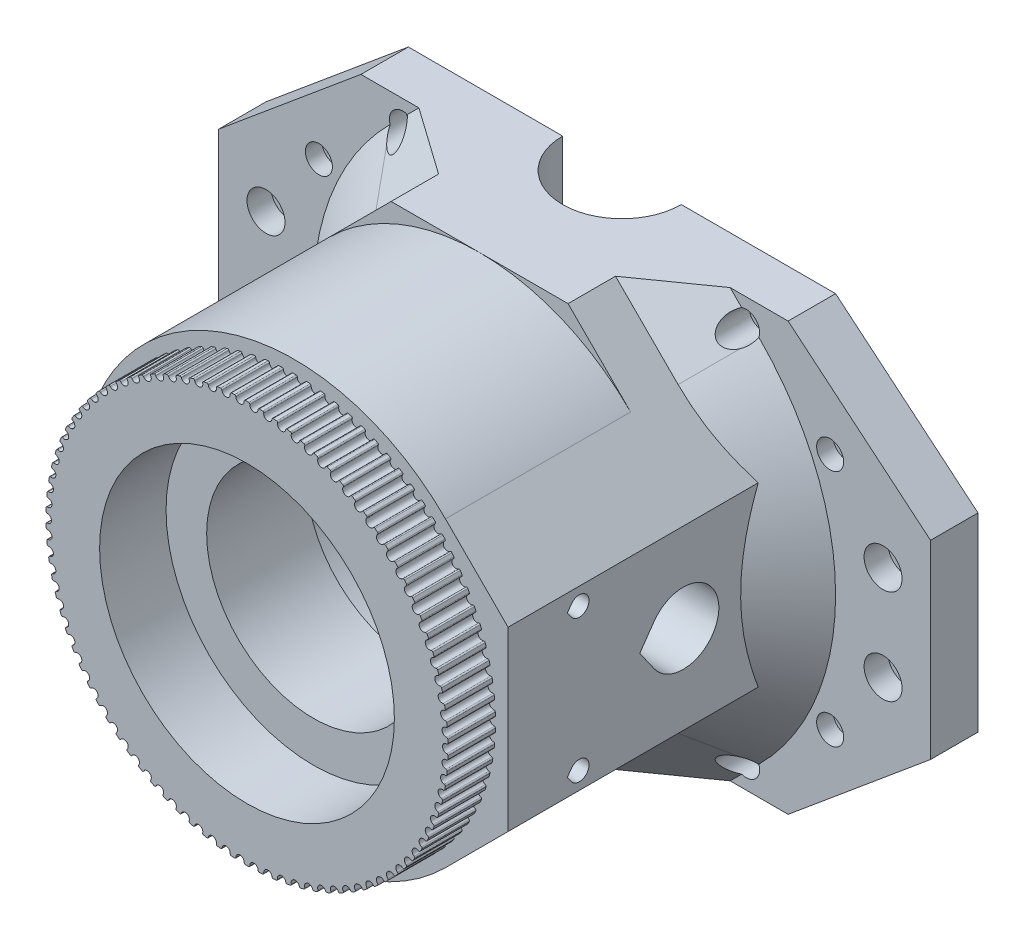
SolidWorks part; units mm, degrees
ref_plane "Front Plane" through (0, 0, 0) normal (1, 0, 0) x (0, 1, 0)
ref_plane "Top Plane" through (0, 0, 0) normal (0, 0, 1) x (0, 1, 0)
ref_plane "Right Plane" through (0, 0, 0) normal (0, 1, 0) x (-1, 0, 0)
sketch "Sketch1" plane through (0, 0, 0) normal (1, 0, 0) x (0, 1, 0)
  line L0 (-45, -80) -> (45, -80)
  line L1 (-31, 0) -> (31, 0)
  line L2 (-31, 0) -> (-31, -14)
  line L3 (-31, -14) -> (31, -14)
  line L4 (31, 0) -> (31, -14)
  line L5 (-31, 0) -> (31, -14) construction
  line L6 (-31, -14) -> (31, 0) construction
  line L7 (-31, -36) -> (31, -36)
  line L8 (-31, -36) -> (-31, -50)
  line L9 (-31, -50) -> (31, -50)
  line L10 (31, -36) -> (31, -50)
  line L11 (-31, -36) -> (31, -50) construction
  line L12 (-31, -50) -> (31, -36) construction
  line L13 (45, -80) -> (45, -1)
  line L14 (45, -1) -> (31, -1)
  line L15 (-31, -1) -> (-45, -1)
  line L16 (-45, -1) -> (-45, -80)
  point P0 (0, -7)
  point P5 (0, -43)
  point P16 (0, 0)
  dimension "D1" = 62
  dimension "D2" = 62
  dimension "D3" = 14
  dimension "D4" = 14
  dimension "D5" = 30
  dimension "D6" = 1
  dimension "D7" = 22
  dimension "D8" = 90
sketch "Sketch2" plane through (0, 0, 0) normal (0, 0, 1) x (0, 1, 0)
  line L0 (-45, 45) -> (-20, 75)
  line L1 (-20, 75) -> (20, 75)
  line L2 (45, 45) -> (-45, 45)
  line L3 (45, 45) -> (45, -45)
  line L4 (45, -45) -> (-45, -45)
  line L5 (-45, 45) -> (-45, -45)
  line L6 (45, 45) -> (-45, -45) construction
  line L7 (45, -45) -> (-45, 45) construction
  line L8 (20, 75) -> (45, 45)
  line L9 (-45, -45) -> (-20, -75)
  line L10 (-20, -75) -> (20, -75)
  line L11 (20, -75) -> (45, -45)
  line L12 (0, 75) -> (0, -75) construction
  line L13 (-45, -18.6396) -> (-18.6396, -45)
  line L14 (-18.6396, 45) -> (-45, 18.6396)
  line L15 (45, 18.6396) -> (18.6396, 45)
  line L16 (18.6396, -45) -> (45, -18.6396)
  circle A0 centre (0, 0) radius 45
  circle A1 centre (0, 0) radius 31.05
  circle A2 centre (0, 0) radius 22.5
  point P15 (0, 0)
  point P27 (0, 0)
  dimension "D1" = 90
  dimension "D2" = 62.1
  dimension "D3" = 45
  dimension "D4" = 150
  dimension "D5" = 40
  dimension "D6" = 4
  dimension "D7" = 45
extrude "Boss-Extrude1" add sketch "Sketch2" against normal up to vertex (80 mm away) from offset 11 contours A0 A1 | A1 A2 region at (-40.3987, 16.7337, 0) region at (0, -30.1718, 0) up to point (0, -45, -80) offset against normal yes
extrude "Boss-Extrude2" add sketch "Sketch2<3>" along normal blind 10 from surface contours A0 L5 L4 | A0 L2 L5 | A0 L4 L3 | A0 L3 L2 | L10 L11 L4 L9 | L8 L1 L0 L2 | A0 L13 L4 | A0 L5 L13 | A0 L4 | A0 L3 | A0 L2 L14 | A0 L14 L5 | A0 L3 L15 | A0 L15 L2 region at (-58.0769, 0, 0) region at (-36.2132, -36.2132, 0) region at (-42.2926, -17.5182, 0) region at (-17.5182, -42.2926, 0) region at (-42.2926, 17.5182, 0) region at (17.5182, -42.2926, 0) region at (-36.2132, 36.2132, 0) region at (-17.5182, 42.2926, 0) region at (36.2132, -36.2132, 0) region at (42.2926, -17.5182, 0) region at (17.5182, 42.2926, 0) region at (58.0769, 0, 0) region at (42.2926, 17.5182, 0) region at (36.2132, 36.2132, 0) starting at face at (45, 0, -80)
sketch "Sketch2<3>" plane through (0, 0, 0) normal (0, 0, 1) x (0, 1, 0) same geometry as "Sketch2"
extrude "Boss-Extrude4" add sketch "Sketch2<6>" along normal blind 20 from surface contours A0 L5 | A0 L5 L13 | A0 L16 L3 | A0 L3 L15 region at (-17.5182, -42.2926, 0) region at (17.5182, -42.2926, 0) region at (-17.5182, 42.2926, 0) region at (17.5182, 42.2926, 0) starting at face at (-47.5, 0, -70)
sketch "Sketch2<6>" plane through (0, 0, 0) normal (0, 0, 1) x (0, 1, 0) same geometry as "Sketch2"
sketch "Sketch5" plane through (0, -45, 0) normal (0, -1, 0) x (1, 0, 0)
  line L0 (-45, -80) -> (45, -80) construction
  circle A0 centre (0, -80) radius 12.5
  line M9 (-45, -80) -> (45, -80)
  dimension "D1" = 25
extrude "Cut-Extrude3" cut sketch "Sketch5" against normal through all contours A0 M9 region at (0, -45, -74.6948)
sketch "Sketch6" plane through (0, 0, -70) normal (0, 0, 1) x (1, 0, 0)
  line L0 (-65, 10) -> (-65, -10) construction
  line L1 (0, 0) -> (-99.7082, 0) construction
  line L2 (65, 10) -> (65, -10) construction
  line L3 (75, -20) -> (75, 20) construction
  line L4 (-75, -20) -> (-75, 20) construction
  circle A0 centre (65, 10) radius 4
  circle A1 centre (65, 10) radius 2.05
  circle A2 centre (-65, 10) radius 2.05
  circle A3 centre (-65, 10) radius 4
  circle A4 centre (-65, -10) radius 2.05
  circle A5 centre (-65, -10) radius 4
  circle A6 centre (65, -10) radius 2.05
  circle A7 centre (65, -10) radius 4
  point P3 (-65, 0)
  point P9 (65, 0)
  dimension "D4" = 8
  dimension "D5" = 4.1
  dimension "D1" = 20
  dimension "D2" = 10
  dimension "D3" = 10
  dimension "D6" = 2
  dimension "D7" = 2
extrude "Cut-Extrude4" cut sketch "Sketch6" against normal through all contours A1 | A4 | A2 | A6
extrude "Cut-Extrude5" cut sketch "Sketch6<4>" against normal blind 5
sketch "Sketch6<4>" plane through (0, 0, -70) normal (0, 0, 1) x (1, 0, 0) same geometry as "Sketch6"
extrude "Cut-Extrude1" cut sketch "Sketch2<4>" against normal blind 15 contours A1
sketch "Sketch2<4>" plane through (0, 0, 0) normal (0, 0, 1) x (0, 1, 0) same geometry as "Sketch2"
extrude "Cut-Extrude2" cut sketch "Sketch2<5>" against normal through all from vertex contours A1 starting at point (0, -31, -36)
sketch "Sketch2<5>" plane through (0, 0, 0) normal (0, 0, 1) x (0, 1, 0) same geometry as "Sketch2"
sketch "Sketch7" plane through (0, 0, -70) normal (0, 0, 1) x (1, 0, 0)
  line L0 (-75, 20) -> (75, 20) construction
  line L1 (-45, 45) -> (-18.6396, 45) construction
  line L2 (-45, 45) -> (0, 45) construction
  line L3 (-30, 45) -> (-60, 20) construction
  line L4 (-75, 20) -> (-45, 45) construction
  line L5 (0, 13.0372) -> (0, -13.0372) construction
  line L6 (-13.0372, 0) -> (13.0372, 0) construction
  line L7 (30, 45) -> (60, 20) construction
  line L8 (30, -45) -> (60, -20) construction
  line L9 (-30, -45) -> (-60, -20) construction
  circle A0 centre (-53.8542, 25.1215) radius 1.6
  circle A1 centre (-53.8542, 25.1215) radius 2.85
  circle A2 centre (-36.1458, 39.8785) radius 2.85
  circle A3 centre (-36.1458, 39.8785) radius 1.6
  circle A4 centre (36.1458, 39.8785) radius 1.6
  circle A5 centre (36.1458, 39.8785) radius 2.85
  circle A6 centre (53.8542, 25.1215) radius 2.85
  circle A7 centre (53.8542, 25.1215) radius 1.6
  circle A8 centre (53.8542, -25.1215) radius 1.6
  circle A9 centre (53.8542, -25.1215) radius 2.85
  circle A10 centre (36.1458, -39.8785) radius 2.85
  circle A11 centre (36.1458, -39.8785) radius 1.6
  circle A12 centre (-36.1458, -39.8785) radius 1.6
  circle A13 centre (-36.1458, -39.8785) radius 2.85
  circle A14 centre (-53.8542, -25.1215) radius 2.85
  circle A15 centre (-53.8542, -25.1215) radius 1.6
  circle A16 centre (-36.1458, -39.8785) radius 5.5
  circle A17 centre (36.1458, -39.8785) radius 5.5
  point P23 (0, 0)
  point P26 (0, 0)
  dimension "D2" = 5.7
  dimension "D3" = 3.2
  dimension "D6" = 3.2
  dimension "D7" = 5.7
  dimension "D8" = 11
  dimension "D9" = 11
  dimension "D1" = 15
  dimension "D4" = 8
  dimension "D5" = 8
extrude "Cut-Extrude6" cut sketch "Sketch7" against normal through all contours A15 | A0 | A3 | A4 | A7 | A8 | A11 | A12
extrude "Cut-Extrude7" cut sketch "Sketch7<3>" against normal blind 3.5 contours A14 | A1 | A2 | A5 | A6 | A9 | A10 | A13
sketch "Sketch7<3>" plane through (0, 0, -70) normal (0, 0, 1) x (1, 0, 0) same geometry as "Sketch7"
chamfer "Chamfer2" distance 10 angle 45 6 edges at (25.2297, -38.4099, -70) (25.2297, 38.4099, -70) (45, 0, -70) (-25.2297, 38.4099, -70) (-25.2297, -38.4099, -70) (-45, 0, -70)
extrude "Boss-Extrude6" add sketch "Sketch2<7>" against normal up to surface (70 mm away) from surface contours A0 L13 L4 | A0 L4 L16 region at (42.2926, -17.5182, 0) region at (42.2926, 17.5182, 0) up to face at (56.7042, -25.1215, -70) starting at face at (31.05, 0, -11)
sketch "Sketch2<7>" plane through (0, 0, 0) normal (0, 0, 1) x (0, 1, 0) same geometry as "Sketch2"
sketch "Sketch8" plane through (45, 0, 0) normal (1, 0, 0) x (0, 1, 0)
  line L0 (-15, -26) -> (-9.9, -26) construction
  line L1 (15, -26) -> (20.2, -26) construction
  line L2 (-15, -26) -> (-20.2, -26) construction
  line L3 (-9.9, -26) -> (15, -26) construction
  line L4 (-9.9, -26) -> (-9.9, -11) construction
  line L5 (18.6396, -11) -> (-18.6396, -11) construction
  line L6 (-20.2, -26) -> (-20.2, -11)
  line L7 (-31.8198, -11) -> (-18.6396, -11) construction
  line L8 (20.2, -26) -> (20.2, -11)
  line L9 (18.6396, -11) -> (31.8198, -11) construction
  line L10 (-14.0823, -24.6894) -> (-15, -24.0468)
  line L11 (-16.1758, -24.3207) -> (-15, -23.4974)
  line L12 (-15.9177, -24.6894) -> (-15, -24.0468)
  line L13 (-13.8242, -24.3207) -> (-15, -23.4974)
  line L14 (-15, -26) -> (-15, -23.4974) construction
  line L15 (16.1758, -24.3207) -> (15, -23.4974)
  line L16 (15, -26) -> (15, -23.4974) construction
  line L17 (14.0823, -24.6894) -> (15, -24.0468)
  line L18 (13.8242, -24.3207) -> (15, -23.4974)
  line L19 (15.9177, -24.6894) -> (15, -24.0468)
  line L20 (-20.2, -11) -> (20.2, -11)
  line L21 (-20.2, -26) -> (-20.2, -32.9)
  line L22 (20.2, -26) -> (20.2, -32.9)
  line L23 (-20.2, -32.9) -> (20.2, -32.9)
  line L24 (0, -47.9) -> (0, -38.7442) construction
  line L25 (-4.3018, -41.7564) -> (0, -38.7442)
  line L26 (4.3018, -41.7564) -> (0, -38.7442)
  arc A0 (-16.1758, -24.3207) -> (-13.8242, -24.3207) centre (-15, -26) ccw
  arc A1 (-15.9177, -24.6894) -> (-14.0823, -24.6894) centre (-15, -26) ccw
  arc A2 (14.0823, -24.6894) -> (15.9177, -24.6894) centre (15, -26) ccw
  arc A3 (13.8242, -24.3207) -> (16.1758, -24.3207) centre (15, -26) ccw
  arc A4 (-4.3018, -41.7564) -> (4.3018, -41.7564) centre (0, -47.9) ccw
  point P29 (0, -11)
  dimension "D6" = 3.2
  dimension "D7" = 4.1
  dimension "D10" = 3.2
  dimension "D11" = 4.1
  dimension "D15" = 15
  dimension "D1" = 15
  dimension "D2" = 24.9
  dimension "D3" = 5.2
  dimension "D4" = 5.1
  dimension "D5" = 5.2
  dimension "D8" = 55
  dimension "D9" = 55
  dimension "D12" = 55
  dimension "D13" = 55
  dimension "D14" = 6.9
  dimension "D16" = 15
  dimension "D17" = 55
sketch "Sketch3" plane through (0, 0, -11) normal (0, 0, 1) x (1, 0, 0)
  line L0 (0, 0) -> (0, 42.3568)
  line L1 (0, 0) -> (1.4374, 41.1617) construction
  line L2 (0, 0) -> (2.9547, 42.2537)
  line L3 (1.4374, 41.1617) -> (1.4678, 42.0312) construction
  arc A0 (0.6589, 42.3517) -> (2.297, 42.2945) centre (1.4678, 42.0312) ccw
  arc A1 (0, 42.3568) -> (0.6589, 42.3517) centre (0, 0) cw
  arc A2 (2.297, 42.2945) -> (2.9547, 42.2537) centre (0, 0) cw
  arc A3 (0, 31.05) -> (2.1659, 30.9744) centre (0, 0) cw
  circle A4 centre (0, 0) radius 31.05 construction
  circle M5 centre (0, 0) radius 31.05
  dimension "D1" = 42.3568
  dimension "D2" = 2
  dimension "D3" = 2
  dimension "D4" = 42.3568
  dimension "D5" = 41.1868
  dimension "D6" = 0.87
extrude "Boss-Extrude3" add sketch "Sketch3" along normal up to vertex (10 mm away) contours A2 A0 A1 L0 L2 M5 region at (1.2803, 36.6619, -11) up to point (0, 45, -1)
fillet "Fillet1" radius 0.26 2 edges at (2.297, 42.2945, -6) (0.6589, 42.3517, -6)
pattern_circular "CirPattern1" count 90 over 360 about axis through (0, 0, -80) along (0, 0, 1) of "Fillet1", "Boss-Extrude3" reverse direction yes
extrude "Cut-Extrude9" cut sketch "Sketch8" against normal blind 7 contours A0 L13 L11 | A3 L15 L18
extrude "Cut-Extrude10" cut sketch "Sketch8<3>" against normal blind 3 from surface contours A1 L10 L12 | A2 L19 L17 starting at face at (38, -15, -25.2894)
sketch "Sketch8<3>" plane through (45, 0, 0) normal (1, 0, 0) x (0, 1, 0) same geometry as "Sketch8"
extrude "Cut-Extrude11" cut sketch "Sketch8<4>" against normal blind 45 contours A4 L26 L25
sketch "Sketch8<4>" plane through (45, 0, 0) normal (1, 0, 0) x (0, 1, 0) same geometry as "Sketch8"
sketch "Sketch11" plane through (0, 0, -11) normal (0, 0, 1) x (1, 0, 0)
  line L0 (45, -18.6396) -> (45, 18.6396) construction
  line L1 (45, 18.6396) -> (31.8198, 31.8198) construction
  line L2 (31.8198, -31.8198) -> (45, -18.6396) construction
  line L3 (45, -18.6396) -> (45, 18.6396)
  line L4 (45, 18.6396) -> (31.8198, 31.8198)
  line L5 (31.8198, -31.8198) -> (45, -18.6396)
  arc A0 (31.8198, 31.8198) -> (31.8198, -31.8198) centre (0, 0) ccw construction
  arc A1 (0.3417, 42.3555) -> (-0.3417, 42.3555) centre (0, 0) ccw construction
  arc A2 (-0.3417, 42.3555) -> (-0.5992, 42.0807) centre (-0.3396, 42.0955) ccw construction
  arc A3 (-2.3377, 42.02) -> (-0.5992, 42.0807) centre (-1.4678, 42.0312) ccw construction
  arc A4 (-2.3377, 42.02) -> (-2.6137, 42.2761) centre (-2.5977, 42.0166) ccw construction
  arc A5 (-2.6137, 42.2761) -> (-3.2954, 42.2284) centre (0, 0) ccw construction
  arc A6 (-3.2954, 42.2284) -> (-3.5331, 41.9364) centre (-3.2752, 41.9692) ccw construction
  arc A7 (-5.2632, 41.7545) -> (-3.5331, 41.9364) centre (-4.3961, 41.8264) ccw construction
  arc A8 (-5.2632, 41.7545) -> (-5.5564, 41.9908) centre (-5.5223, 41.7331) ccw construction
  arc A9 (-5.5564, 41.9908) -> (-6.2331, 41.8957) centre (0, 0) ccw construction
  arc A10 (-6.2331, 41.8957) -> (-6.4498, 41.5878) centre (-6.1948, 41.6385) ccw construction
  arc A11 (-8.163, 41.2857) -> (-6.4498, 41.5878) centre (-7.3031, 41.4179) ccw construction
  arc A12 (-8.163, 41.2857) -> (-8.472, 41.5009) centre (-8.42, 41.2462) ccw construction
  arc A13 (-8.472, 41.5009) -> (-9.1404, 41.3588) centre (0, 0) ccw construction
  arc A14 (-9.1404, 41.3588) -> (-9.3351, 41.0365) centre (-9.0843, 41.105) ccw construction
  arc A15 (-11.023, 40.6157) -> (-9.3351, 41.0365) centre (-10.1745, 40.8076) ccw construction
  arc A16 (-11.023, 40.6157) -> (-11.3463, 40.8089) centre (-11.2766, 40.5584) ccw construction
  arc A17 (-11.3463, 40.8089) -> (-12.0032, 40.6205) centre (0, 0) ccw construction
  arc A18 (-12.0032, 40.6205) -> (-12.175, 40.2854) centre (-11.9295, 40.3712) ccw construction
  arc A19 (-13.8294, 39.7478) -> (-12.175, 40.2854) centre (-12.9963, 39.9984) ccw construction
  arc A20 (-13.8294, 39.7478) -> (-14.1653, 39.918) centre (-14.0784, 39.6729) ccw construction
  arc A21 (-14.1653, 39.918) -> (-14.8075, 39.6842) centre (0, 0) ccw construction
  arc A22 (-14.8075, 39.6842) -> (-14.9555, 39.338) centre (-14.7166, 39.4407) ccw construction
  arc A23 (-16.5684, 38.6863) -> (-14.9555, 39.338) centre (-15.7548, 38.9944) ccw construction
  arc A24 (-16.5684, 38.6863) -> (-16.9154, 38.8326) centre (-16.8115, 38.5942) ccw construction
  arc A25 (-16.9154, 38.8326) -> (-17.5397, 38.5547) centre (0, 0) ccw construction
  arc A26 (-17.5397, 38.5547) -> (-17.6631, 38.1989) centre (-17.432, 38.318) ccw construction
  arc A27 (-19.2266, 37.4363) -> (-17.6631, 38.1989) centre (-18.4365, 37.8004) ccw construction
  arc A28 (-19.2266, 37.4363) -> (-19.583, 37.5581) centre (-19.4628, 37.3275) ccw construction
  arc A29 (-19.583, 37.5581) -> (-20.1864, 37.2372) centre (0, 0) ccw construction
  arc A30 (-20.1864, 37.2372) -> (-20.2847, 36.8737) centre (-20.0625, 37.0087) ccw construction
  arc A31 (-21.7912, 36.004) -> (-20.2847, 36.8737) centre (-21.0284, 36.4223) ccw construction
  arc A32 (-21.7912, 36.004) -> (-22.1552, 36.1005) centre (-22.0192, 35.8789) ccw construction
  arc A33 (-22.1552, 36.1005) -> (-22.7347, 35.7384) centre (0, 0) ccw construction
  arc A34 (-22.7347, 35.7384) -> (-22.8075, 35.3689) centre (-22.5952, 35.519) ccw construction
  arc A35 (-24.2497, 34.3962) -> (-22.8075, 35.3689) centre (-23.5179, 34.8667) ccw construction
  arc A36 (-24.2497, 34.3962) -> (-24.6195, 34.4671) centre (-24.4684, 34.2556) ccw construction
  arc A37 (-24.6195, 34.4671) -> (-25.1723, 34.0654) centre (0, 0) ccw construction
  arc A38 (-25.1723, 34.0654) -> (-25.2191, 33.6918) centre (-25.0178, 33.8563) ccw construction
  arc A39 (-26.59, 32.6208) -> (-25.2191, 33.6918) centre (-25.8928, 33.1412) ccw construction
  arc A40 (-26.59, 32.6208) -> (-26.9638, 32.6658) centre (-26.7983, 32.4653) ccw construction
  arc A41 (-26.9638, 32.6658) -> (-27.4873, 32.2265) centre (0, 0) ccw construction
  arc A42 (-27.4873, 32.2265) -> (-27.5079, 31.8505) centre (-27.3186, 32.0287) ccw construction
  arc A43 (-28.8007, 30.6865) -> (-27.5079, 31.8505) centre (-28.1415, 31.2543) ccw construction
  arc A44 (-28.8007, 30.6865) -> (-29.1768, 30.7053) centre (-28.9977, 30.5168) ccw construction
  arc A45 (-29.1768, 30.7053) -> (-29.6684, 30.2306) centre (0, 0) ccw construction
  arc A46 (-29.6684, 30.2306) -> (-29.6627, 29.8541) centre (-29.4862, 30.045) ccw construction
  arc A47 (-30.8711, 28.6027) -> (-29.6627, 29.8541) centre (-30.2532, 29.2151) ccw construction
  arc A48 (-30.8711, 28.6027) -> (-31.2476, 28.5953) centre (-31.0558, 28.4197) ccw construction
  arc A49 (-31.2476, 28.5953) -> (-31.7049, 28.0874) centre (0, 0) ccw construction
  arc A50 (-31.7049, 28.0874) -> (-31.673, 27.7122) centre (-31.5103, 27.915) ccw construction
  arc A51 (-32.7911, 26.3796) -> (-31.673, 27.7122) centre (-32.2174, 27.0336) ccw construction
  arc A52 (-32.7911, 26.3796) -> (-33.1662, 26.3459) centre (-32.9626, 26.1842) ccw construction
  arc A53 (-33.1662, 26.3459) -> (-33.5869, 25.8074) centre (0, 0) ccw construction
  arc A54 (-33.5869, 25.8074) -> (-33.5289, 25.4353) centre (-33.3808, 25.649) ccw construction
  arc A55 (-34.5514, 24.028) -> (-33.5289, 25.4353) centre (-34.0247, 24.7204) ccw construction
  arc A56 (-34.5514, 24.028) -> (-34.9232, 23.9681) centre (-34.7088, 23.821) ccw construction
  arc A57 (-34.9232, 23.9681) -> (-35.3053, 23.4016) centre (0, 0) ccw construction
  arc A58 (-35.3053, 23.4016) -> (-35.2215, 23.0345) centre (-35.0886, 23.258) ccw construction
  arc A59 (-36.1434, 21.5592) -> (-35.2215, 23.0345) centre (-35.6662, 22.2867) ccw construction
  arc A60 (-36.1434, 21.5592) -> (-36.5101, 21.4736) centre (-36.2859, 21.3418) ccw construction
  arc A61 (-36.5101, 21.4736) -> (-36.8517, 20.8818) centre (0, 0) ccw construction
  arc A62 (-36.8517, 20.8818) -> (-36.7425, 20.5214) centre (-36.6255, 20.7536) ccw construction
  arc A63 (-37.5592, 18.9855) -> (-36.7425, 20.5214) centre (-37.134, 19.7445) ccw construction
  arc A64 (-37.5592, 18.9855) -> (-37.919, 18.8745) centre (-37.6863, 18.7587) ccw construction
  arc A65 (-37.919, 18.8745) -> (-38.2186, 18.2603) centre (0, 0) ccw construction
  arc A66 (-38.2186, 18.2603) -> (-38.0845, 17.9084) centre (-37.984, 18.1482) ccw construction
  arc A67 (-38.7921, 16.3192) -> (-38.0845, 17.9084) centre (-38.4208, 17.1061) ccw construction
  arc A68 (-38.7921, 16.3192) -> (-39.1433, 16.1834) centre (-38.903, 16.0841) ccw construction
  arc A69 (-39.1433, 16.1834) -> (-39.3993, 15.5498) centre (0, 0) ccw construction
  arc A70 (-39.3993, 15.5498) -> (-39.241, 15.2082) centre (-39.1574, 15.4544) ccw construction
  arc A71 (-39.836, 13.5735) -> (-39.241, 15.2082) centre (-39.5205, 14.3843) ccw construction
  arc A72 (-39.836, 13.5735) -> (-40.1768, 13.4135) centre (-39.9302, 13.3312) ccw construction
  arc A73 (-40.1768, 13.4135) -> (-40.388, 12.7636) centre (0, 0) ccw construction
  arc A74 (-40.388, 12.7636) -> (-40.2063, 12.4338) centre (-40.1401, 12.6852) ccw construction
  arc A75 (-40.6858, 10.7616) -> (-40.2063, 12.4338) centre (-40.4276, 11.5924) ccw construction
  arc A76 (-40.6858, 10.7616) -> (-41.0147, 10.5783) centre (-40.7629, 10.5133) ccw construction
  arc A77 (-41.0147, 10.5783) -> (-41.18, 9.9152) centre (0, 0) ccw construction
  arc A78 (-41.18, 9.9152) -> (-40.9757, 9.5989) centre (-40.9272, 9.8543) ccw construction
  arc A79 (-41.3373, 7.8973) -> (-40.9757, 9.5989) centre (-41.1378, 8.7441) ccw construction
  arc A80 (-41.3373, 7.8973) -> (-41.6526, 7.6914) centre (-41.397, 7.6442) ccw construction
  arc A81 (-41.6526, 7.6914) -> (-41.7713, 7.0185) centre (0, 0) ccw construction
  arc A82 (-41.7713, 7.0185) -> (-41.5454, 6.7172) centre (-41.5149, 6.9754) ccw construction
  arc A83 (-41.7875, 4.9945) -> (-41.5454, 6.7172) centre (-41.6475, 5.8532) ccw construction
  arc A84 (-41.7875, 4.9945) -> (-42.0877, 4.7672) centre (-41.8294, 4.7379) ccw construction
  arc A85 (-42.0877, 4.7672) -> (-42.1591, 4.0875) centre (0, 0) ccw construction
  arc A86 (-42.1591, 4.0875) -> (-41.9128, 3.8027) centre (-41.9004, 4.0624) ccw construction
  arc A87 (-42.0341, 2.0674) -> (-41.9128, 3.8027) centre (-41.9544, 2.9337) ccw construction
  arc A88 (-42.0341, 2.0674) -> (-42.3177, 1.8197) centre (-42.058, 1.8085) ccw construction
  arc A89 (-42.3177, 1.8197) -> (-42.3416, 1.1367) centre (0, 0) ccw construction
  arc A90 (-42.3416, 1.1367) -> (-42.076, 0.8698) centre (-42.0817, 1.1297) ccw construction
  arc A91 (-42.076, -0.8698) -> (-42.076, 0.8698) centre (-42.0568, 0) ccw construction
  arc A92 (-42.076, -0.8698) -> (-42.3416, -1.1367) centre (-42.0817, -1.1297) ccw construction
  arc A93 (-42.3416, -1.1367) -> (-42.3177, -1.8197) centre (0, 0) ccw construction
  arc A94 (-42.3177, -1.8197) -> (-42.0341, -2.0674) centre (-42.058, -1.8085) ccw construction
  arc A95 (-41.9128, -3.8027) -> (-42.0341, -2.0674) centre (-41.9544, -2.9337) ccw construction
  arc A96 (-41.9128, -3.8027) -> (-42.1591, -4.0875) centre (-41.9004, -4.0624) ccw construction
  arc A97 (-42.1591, -4.0875) -> (-42.0877, -4.7672) centre (0, 0) ccw construction
  arc A98 (-42.0877, -4.7672) -> (-41.7875, -4.9945) centre (-41.8294, -4.7379) ccw construction
  arc A99 (-41.5454, -6.7172) -> (-41.7875, -4.9945) centre (-41.6475, -5.8532) ccw construction
  arc A100 (-41.5454, -6.7172) -> (-41.7713, -7.0185) centre (-41.5149, -6.9754) ccw construction
  arc A101 (-41.7713, -7.0185) -> (-41.6526, -7.6914) centre (0, 0) ccw construction
  arc A102 (-41.6526, -7.6914) -> (-41.3373, -7.8973) centre (-41.397, -7.6442) ccw construction
  arc A103 (-40.9757, -9.5989) -> (-41.3373, -7.8973) centre (-41.1378, -8.7441) ccw construction
  arc A104 (-40.9757, -9.5989) -> (-41.18, -9.9152) centre (-40.9272, -9.8543) ccw construction
  arc A105 (-41.18, -9.9152) -> (-41.0147, -10.5783) centre (0, 0) ccw construction
  arc A106 (-41.0147, -10.5783) -> (-40.6858, -10.7616) centre (-40.7629, -10.5133) ccw construction
  arc A107 (-40.2063, -12.4338) -> (-40.6858, -10.7616) centre (-40.4276, -11.5924) ccw construction
  arc A108 (-40.2063, -12.4338) -> (-40.388, -12.7636) centre (-40.1401, -12.6852) ccw construction
  arc A109 (-40.388, -12.7636) -> (-40.1768, -13.4135) centre (0, 0) ccw construction
  arc A110 (-40.1768, -13.4135) -> (-39.836, -13.5735) centre (-39.9302, -13.3312) ccw construction
  arc A111 (-39.241, -15.2082) -> (-39.836, -13.5735) centre (-39.5205, -14.3843) ccw construction
  arc A112 (-39.241, -15.2082) -> (-39.3993, -15.5498) centre (-39.1574, -15.4544) ccw construction
  arc A113 (-39.3993, -15.5498) -> (-39.1433, -16.1834) centre (0, 0) ccw construction
  arc A114 (-39.1433, -16.1834) -> (-38.7921, -16.3192) centre (-38.903, -16.0841) ccw construction
  arc A115 (-38.0845, -17.9084) -> (-38.7921, -16.3192) centre (-38.4208, -17.1061) ccw construction
  arc A116 (-38.0845, -17.9084) -> (-38.2186, -18.2603) centre (-37.984, -18.1482) ccw construction
  arc A117 (-38.2186, -18.2603) -> (-37.919, -18.8745) centre (0, 0) ccw construction
  arc A118 (-37.919, -18.8745) -> (-37.5592, -18.9855) centre (-37.6863, -18.7587) ccw construction
  arc A119 (-36.7425, -20.5214) -> (-37.5592, -18.9855) centre (-37.134, -19.7445) ccw construction
  arc A120 (-36.7425, -20.5214) -> (-36.8517, -20.8818) centre (-36.6255, -20.7536) ccw construction
  arc A121 (-36.8517, -20.8818) -> (-36.5101, -21.4736) centre (0, 0) ccw construction
  arc A122 (-36.5101, -21.4736) -> (-36.1434, -21.5592) centre (-36.2859, -21.3418) ccw construction
  arc A123 (-35.2215, -23.0345) -> (-36.1434, -21.5592) centre (-35.6662, -22.2867) ccw construction
  arc A124 (-35.2215, -23.0345) -> (-35.3053, -23.4016) centre (-35.0886, -23.258) ccw construction
  arc A125 (-35.3053, -23.4016) -> (-34.9232, -23.9681) centre (0, 0) ccw construction
  arc A126 (-34.9232, -23.9681) -> (-34.5514, -24.028) centre (-34.7088, -23.821) ccw construction
  arc A127 (-33.5289, -25.4353) -> (-34.5514, -24.028) centre (-34.0247, -24.7204) ccw construction
  arc A128 (-33.5289, -25.4353) -> (-33.5869, -25.8074) centre (-33.3808, -25.649) ccw construction
  arc A129 (-33.5869, -25.8074) -> (-33.1662, -26.3459) centre (0, 0) ccw construction
  arc A130 (-33.1662, -26.3459) -> (-32.7911, -26.3796) centre (-32.9626, -26.1842) ccw construction
  arc A131 (-31.673, -27.7122) -> (-32.7911, -26.3796) centre (-32.2174, -27.0336) ccw construction
  arc A132 (-31.673, -27.7122) -> (-31.7049, -28.0874) centre (-31.5103, -27.915) ccw construction
  arc A133 (-31.7049, -28.0874) -> (-31.2476, -28.5953) centre (0, 0) ccw construction
  arc A134 (-31.2476, -28.5953) -> (-30.8711, -28.6027) centre (-31.0558, -28.4197) ccw construction
  arc A135 (-29.6627, -29.8541) -> (-30.8711, -28.6027) centre (-30.2532, -29.2151) ccw construction
  arc A136 (-29.6627, -29.8541) -> (-29.6684, -30.2306) centre (-29.4862, -30.045) ccw construction
  arc A137 (-29.6684, -30.2306) -> (-29.1768, -30.7053) centre (0, 0) ccw construction
  arc A138 (-29.1768, -30.7053) -> (-28.8007, -30.6865) centre (-28.9977, -30.5168) ccw construction
  arc A139 (-27.5079, -31.8505) -> (-28.8007, -30.6865) centre (-28.1415, -31.2543) ccw construction
  arc A140 (-27.5079, -31.8505) -> (-27.4873, -32.2265) centre (-27.3186, -32.0287) ccw construction
  arc A141 (-27.4873, -32.2265) -> (-26.9638, -32.6658) centre (0, 0) ccw construction
  arc A142 (-26.9638, -32.6658) -> (-26.59, -32.6208) centre (-26.7983, -32.4653) ccw construction
  arc A143 (-25.2191, -33.6918) -> (-26.59, -32.6208) centre (-25.8928, -33.1412) ccw construction
  arc A144 (-25.2191, -33.6918) -> (-25.1723, -34.0654) centre (-25.0178, -33.8563) ccw construction
  arc A145 (-25.1723, -34.0654) -> (-24.6195, -34.4671) centre (0, 0) ccw construction
  arc A146 (-24.6195, -34.4671) -> (-24.2497, -34.3962) centre (-24.4684, -34.2556) ccw construction
  arc A147 (-22.8075, -35.3689) -> (-24.2497, -34.3962) centre (-23.5179, -34.8667) ccw construction
  arc A148 (-22.8075, -35.3689) -> (-22.7347, -35.7384) centre (-22.5952, -35.519) ccw construction
  arc A149 (-22.7347, -35.7384) -> (-22.1552, -36.1005) centre (0, 0) ccw construction
  arc A150 (-22.1552, -36.1005) -> (-21.7912, -36.004) centre (-22.0192, -35.8789) ccw construction
  arc A151 (-20.2847, -36.8737) -> (-21.7912, -36.004) centre (-21.0284, -36.4223) ccw construction
  arc A152 (-20.2847, -36.8737) -> (-20.1864, -37.2372) centre (-20.0625, -37.0087) ccw construction
  arc A153 (-20.1864, -37.2372) -> (-19.583, -37.5581) centre (0, 0) ccw construction
  arc A154 (-19.583, -37.5581) -> (-19.2266, -37.4363) centre (-19.4628, -37.3275) ccw construction
  arc A155 (-17.6631, -38.1989) -> (-19.2266, -37.4363) centre (-18.4365, -37.8004) ccw construction
  arc A156 (-17.6631, -38.1989) -> (-17.5397, -38.5547) centre (-17.432, -38.318) ccw construction
  arc A157 (-17.5397, -38.5547) -> (-16.9154, -38.8326) centre (0, 0) ccw construction
  arc A158 (-16.9154, -38.8326) -> (-16.5684, -38.6863) centre (-16.8115, -38.5942) ccw construction
  arc A159 (-14.9555, -39.338) -> (-16.5684, -38.6863) centre (-15.7548, -38.9944) ccw construction
  arc A160 (-14.9555, -39.338) -> (-14.8075, -39.6842) centre (-14.7166, -39.4407) ccw construction
  arc A161 (-14.8075, -39.6842) -> (-14.1653, -39.918) centre (0, 0) ccw construction
  arc A162 (-14.1653, -39.918) -> (-13.8294, -39.7478) centre (-14.0784, -39.6729) ccw construction
  arc A163 (-12.175, -40.2854) -> (-13.8294, -39.7478) centre (-12.9963, -39.9984) ccw construction
  arc A164 (-12.175, -40.2854) -> (-12.0032, -40.6205) centre (-11.9295, -40.3712) ccw construction
  arc A165 (-12.0032, -40.6205) -> (-11.3463, -40.8089) centre (0, 0) ccw construction
  arc A166 (-11.3463, -40.8089) -> (-11.023, -40.6157) centre (-11.2766, -40.5584) ccw construction
  arc A167 (-9.3351, -41.0365) -> (-11.023, -40.6157) centre (-10.1745, -40.8076) ccw construction
  arc A168 (-9.3351, -41.0365) -> (-9.1404, -41.3588) centre (-9.0843, -41.105) ccw construction
  arc A169 (-9.1404, -41.3588) -> (-8.472, -41.5009) centre (0, 0) ccw construction
  arc A170 (-8.472, -41.5009) -> (-8.163, -41.2857) centre (-8.42, -41.2462) ccw construction
  arc A171 (-6.4498, -41.5878) -> (-8.163, -41.2857) centre (-7.3031, -41.4179) ccw construction
  arc A172 (-6.4498, -41.5878) -> (-6.2331, -41.8957) centre (-6.1948, -41.6385) ccw construction
  arc A173 (-6.2331, -41.8957) -> (-5.5564, -41.9908) centre (0, 0) ccw construction
  arc A174 (-5.5564, -41.9908) -> (-5.2632, -41.7545) centre (-5.5223, -41.7331) ccw construction
  arc A175 (-3.5331, -41.9364) -> (-5.2632, -41.7545) centre (-4.3961, -41.8264) ccw construction
  arc A176 (-3.5331, -41.9364) -> (-3.2954, -42.2284) centre (-3.2752, -41.9692) ccw construction
  arc A177 (-3.2954, -42.2284) -> (-2.6137, -42.2761) centre (0, 0) ccw construction
  arc A178 (-2.6137, -42.2761) -> (-2.3377, -42.02) centre (-2.5977, -42.0166) ccw construction
  arc A179 (-0.5992, -42.0807) -> (-2.3377, -42.02) centre (-1.4678, -42.0312) ccw construction
  arc A180 (-0.5992, -42.0807) -> (-0.3417, -42.3555) centre (-0.3396, -42.0955) ccw construction
  arc A181 (-0.3417, -42.3555) -> (0.3417, -42.3555) centre (0, 0) ccw construction
  arc A182 (0.3417, -42.3555) -> (0.5992, -42.0807) centre (0.3396, -42.0955) ccw construction
  arc A183 (2.3377, -42.02) -> (0.5992, -42.0807) centre (1.4678, -42.0312) ccw construction
  arc A184 (2.3377, -42.02) -> (2.6137, -42.2761) centre (2.5977, -42.0166) ccw construction
  arc A185 (2.6137, -42.2761) -> (3.2954, -42.2284) centre (0, 0) ccw construction
  arc A186 (3.2954, -42.2284) -> (3.5331, -41.9364) centre (3.2752, -41.9692) ccw construction
  arc A187 (5.2632, -41.7545) -> (3.5331, -41.9364) centre (4.3961, -41.8264) ccw construction
  arc A188 (5.2632, -41.7545) -> (5.5564, -41.9908) centre (5.5223, -41.7331) ccw construction
  arc A189 (5.5564, -41.9908) -> (6.2331, -41.8957) centre (0, 0) ccw construction
  arc A190 (6.2331, -41.8957) -> (6.4498, -41.5878) centre (6.1948, -41.6385) ccw construction
  arc A191 (8.163, -41.2857) -> (6.4498, -41.5878) centre (7.3031, -41.4179) ccw construction
  arc A192 (8.163, -41.2857) -> (8.472, -41.5009) centre (8.42, -41.2462) ccw construction
  arc A193 (8.472, -41.5009) -> (9.1404, -41.3588) centre (0, 0) ccw construction
  arc A194 (9.1404, -41.3588) -> (9.3351, -41.0365) centre (9.0843, -41.105) ccw construction
  arc A195 (11.023, -40.6157) -> (9.3351, -41.0365) centre (10.1745, -40.8076) ccw construction
  arc A196 (11.023, -40.6157) -> (11.3463, -40.8089) centre (11.2766, -40.5584) ccw construction
  arc A197 (11.3463, -40.8089) -> (12.0032, -40.6205) centre (0, 0) ccw construction
  arc A198 (12.0032, -40.6205) -> (12.175, -40.2854) centre (11.9295, -40.3712) ccw construction
  arc A199 (13.8294, -39.7478) -> (12.175, -40.2854) centre (12.9963, -39.9984) ccw construction
  arc A200 (13.8294, -39.7478) -> (14.1653, -39.918) centre (14.0784, -39.6729) ccw construction
  arc A201 (14.1653, -39.918) -> (14.8075, -39.6842) centre (0, 0) ccw construction
  arc A202 (14.8075, -39.6842) -> (14.9555, -39.338) centre (14.7166, -39.4407) ccw construction
  arc A203 (16.5684, -38.6863) -> (14.9555, -39.338) centre (15.7548, -38.9944) ccw construction
  arc A204 (16.5684, -38.6863) -> (16.9154, -38.8326) centre (16.8115, -38.5942) ccw construction
  arc A205 (16.9154, -38.8326) -> (17.5397, -38.5547) centre (0, 0) ccw construction
  arc A206 (17.5397, -38.5547) -> (17.6631, -38.1989) centre (17.432, -38.318) ccw construction
  arc A207 (19.2266, -37.4363) -> (17.6631, -38.1989) centre (18.4365, -37.8004) ccw construction
  arc A208 (19.2266, -37.4363) -> (19.583, -37.5581) centre (19.4628, -37.3275) ccw construction
  arc A209 (19.583, -37.5581) -> (20.1864, -37.2372) centre (0, 0) ccw construction
  arc A210 (20.1864, -37.2372) -> (20.2847, -36.8737) centre (20.0625, -37.0087) ccw construction
  arc A211 (21.7912, -36.004) -> (20.2847, -36.8737) centre (21.0284, -36.4223) ccw construction
  arc A212 (21.7912, -36.004) -> (22.1552, -36.1005) centre (22.0192, -35.8789) ccw construction
  arc A213 (22.1552, -36.1005) -> (22.7347, -35.7384) centre (0, 0) ccw construction
  arc A214 (22.7347, -35.7384) -> (22.8075, -35.3689) centre (22.5952, -35.519) ccw construction
  arc A215 (24.2497, -34.3962) -> (22.8075, -35.3689) centre (23.5179, -34.8667) ccw construction
  arc A216 (24.2497, -34.3962) -> (24.6195, -34.4671) centre (24.4684, -34.2556) ccw construction
  arc A217 (24.6195, -34.4671) -> (25.1723, -34.0654) centre (0, 0) ccw construction
  arc A218 (25.1723, -34.0654) -> (25.2191, -33.6918) centre (25.0178, -33.8563) ccw construction
  arc A219 (26.59, -32.6208) -> (25.2191, -33.6918) centre (25.8928, -33.1412) ccw construction
  arc A220 (26.59, -32.6208) -> (26.9638, -32.6658) centre (26.7983, -32.4653) ccw construction
  arc A221 (26.9638, -32.6658) -> (27.4873, -32.2265) centre (0, 0) ccw construction
  arc A222 (27.4873, -32.2265) -> (27.5079, -31.8505) centre (27.3186, -32.0287) ccw construction
  arc A223 (28.8007, -30.6865) -> (27.5079, -31.8505) centre (28.1415, -31.2543) ccw construction
  arc A224 (28.8007, -30.6865) -> (29.1768, -30.7053) centre (28.9977, -30.5168) ccw construction
  arc A225 (29.1768, -30.7053) -> (29.6684, -30.2306) centre (0, 0) ccw construction
  arc A226 (29.6684, -30.2306) -> (29.6627, -29.8541) centre (29.4862, -30.045) ccw construction
  arc A227 (30.8711, -28.6027) -> (29.6627, -29.8541) centre (30.2532, -29.2151) ccw construction
  arc A228 (30.8711, -28.6027) -> (31.2476, -28.5953) centre (31.0558, -28.4197) ccw construction
  arc A229 (31.2476, -28.5953) -> (31.7049, -28.0874) centre (0, 0) ccw construction
  arc A230 (31.7049, -28.0874) -> (31.673, -27.7122) centre (31.5103, -27.915) ccw construction
  arc A231 (32.7911, -26.3796) -> (31.673, -27.7122) centre (32.2174, -27.0336) ccw construction
  arc A232 (32.7911, -26.3796) -> (33.1662, -26.3459) centre (32.9626, -26.1842) ccw construction
  arc A233 (33.1662, -26.3459) -> (33.5869, -25.8074) centre (0, 0) ccw construction
  arc A234 (33.5869, -25.8074) -> (33.5289, -25.4353) centre (33.3808, -25.649) ccw construction
  arc A235 (34.5514, -24.028) -> (33.5289, -25.4353) centre (34.0247, -24.7204) ccw construction
  arc A236 (34.5514, -24.028) -> (34.9232, -23.9681) centre (34.7088, -23.821) ccw construction
  arc A237 (34.9232, -23.9681) -> (35.3053, -23.4016) centre (0, 0) ccw construction
  arc A238 (35.3053, -23.4016) -> (35.2215, -23.0345) centre (35.0886, -23.258) ccw construction
  arc A239 (36.1434, -21.5592) -> (35.2215, -23.0345) centre (35.6662, -22.2867) ccw construction
  arc A240 (36.1434, -21.5592) -> (36.5101, -21.4736) centre (36.2859, -21.3418) ccw construction
  arc A241 (36.5101, -21.4736) -> (36.8517, -20.8818) centre (0, 0) ccw construction
  arc A242 (36.8517, -20.8818) -> (36.7425, -20.5214) centre (36.6255, -20.7536) ccw construction
  arc A243 (37.5592, -18.9855) -> (36.7425, -20.5214) centre (37.134, -19.7445) ccw construction
  arc A244 (37.5592, -18.9855) -> (37.919, -18.8745) centre (37.6863, -18.7587) ccw construction
  arc A245 (37.919, -18.8745) -> (38.2186, -18.2603) centre (0, 0) ccw construction
  arc A246 (38.2186, -18.2603) -> (38.0845, -17.9084) centre (37.984, -18.1482) ccw construction
  arc A247 (38.7921, -16.3192) -> (38.0845, -17.9084) centre (38.4208, -17.1061) ccw construction
  arc A248 (38.7921, -16.3192) -> (39.1433, -16.1834) centre (38.903, -16.0841) ccw construction
  arc A249 (39.1433, -16.1834) -> (39.3993, -15.5498) centre (0, 0) ccw construction
  arc A250 (39.3993, -15.5498) -> (39.241, -15.2082) centre (39.1574, -15.4544) ccw construction
  arc A251 (39.836, -13.5735) -> (39.241, -15.2082) centre (39.5205, -14.3843) ccw construction
  arc A252 (39.836, -13.5735) -> (40.1768, -13.4135) centre (39.9302, -13.3312) ccw construction
  arc A253 (40.1768, -13.4135) -> (40.388, -12.7636) centre (0, 0) ccw construction
  arc A254 (40.388, -12.7636) -> (40.2063, -12.4338) centre (40.1401, -12.6852) ccw construction
  arc A255 (40.6858, -10.7616) -> (40.2063, -12.4338) centre (40.4276, -11.5924) ccw construction
  arc A256 (40.6858, -10.7616) -> (41.0147, -10.5783) centre (40.7629, -10.5133) ccw construction
  arc A257 (41.0147, -10.5783) -> (41.18, -9.9152) centre (0, 0) ccw construction
  arc A258 (41.18, -9.9152) -> (40.9757, -9.5989) centre (40.9272, -9.8543) ccw construction
  arc A259 (41.3373, -7.8973) -> (40.9757, -9.5989) centre (41.1378, -8.7441) ccw construction
  arc A260 (41.3373, -7.8973) -> (41.6526, -7.6914) centre (41.397, -7.6442) ccw construction
  arc A261 (41.6526, -7.6914) -> (41.7713, -7.0185) centre (0, 0) ccw construction
  arc A262 (41.7713, -7.0185) -> (41.5454, -6.7172) centre (41.5149, -6.9754) ccw construction
  arc A263 (41.7875, -4.9945) -> (41.5454, -6.7172) centre (41.6475, -5.8532) ccw construction
  arc A264 (41.7875, -4.9945) -> (42.0877, -4.7672) centre (41.8294, -4.7379) ccw construction
  arc A265 (42.0877, -4.7672) -> (42.1591, -4.0875) centre (0, 0) ccw construction
  arc A266 (42.1591, -4.0875) -> (41.9128, -3.8027) centre (41.9004, -4.0624) ccw construction
  arc A267 (42.0341, -2.0674) -> (41.9128, -3.8027) centre (41.9544, -2.9337) ccw construction
  arc A268 (42.0341, -2.0674) -> (42.3177, -1.8197) centre (42.058, -1.8085) ccw construction
  arc A269 (42.3177, -1.8197) -> (42.3416, -1.1367) centre (0, 0) ccw construction
  arc A270 (42.3416, -1.1367) -> (42.076, -0.8698) centre (42.0817, -1.1297) ccw construction
  arc A271 (42.076, 0.8698) -> (42.076, -0.8698) centre (42.0568, 0) ccw construction
  arc A272 (42.076, 0.8698) -> (42.3416, 1.1367) centre (42.0817, 1.1297) ccw construction
  arc A273 (42.3416, 1.1367) -> (42.3177, 1.8197) centre (0, 0) ccw construction
  arc A274 (42.3177, 1.8197) -> (42.0341, 2.0674) centre (42.058, 1.8085) ccw construction
  arc A275 (41.9128, 3.8027) -> (42.0341, 2.0674) centre (41.9544, 2.9337) ccw construction
  arc A276 (41.9128, 3.8027) -> (42.1591, 4.0875) centre (41.9004, 4.0624) ccw construction
  arc A277 (42.1591, 4.0875) -> (42.0877, 4.7672) centre (0, 0) ccw construction
  arc A278 (42.0877, 4.7672) -> (41.7875, 4.9945) centre (41.8294, 4.7379) ccw construction
  arc A279 (41.5454, 6.7172) -> (41.7875, 4.9945) centre (41.6475, 5.8532) ccw construction
  arc A280 (41.5454, 6.7172) -> (41.7713, 7.0185) centre (41.5149, 6.9754) ccw construction
  arc A281 (41.7713, 7.0185) -> (41.6526, 7.6914) centre (0, 0) ccw construction
  arc A282 (41.6526, 7.6914) -> (41.3373, 7.8973) centre (41.397, 7.6442) ccw construction
  arc A283 (40.9757, 9.5989) -> (41.3373, 7.8973) centre (41.1378, 8.7441) ccw construction
  arc A284 (40.9757, 9.5989) -> (41.18, 9.9152) centre (40.9272, 9.8543) ccw construction
  arc A285 (41.18, 9.9152) -> (41.0147, 10.5783) centre (0, 0) ccw construction
  arc A286 (41.0147, 10.5783) -> (40.6858, 10.7616) centre (40.7629, 10.5133) ccw construction
  arc A287 (40.2063, 12.4338) -> (40.6858, 10.7616) centre (40.4276, 11.5924) ccw construction
  arc A288 (40.2063, 12.4338) -> (40.388, 12.7636) centre (40.1401, 12.6852) ccw construction
  arc A289 (40.388, 12.7636) -> (40.1768, 13.4135) centre (0, 0) ccw construction
  arc A290 (40.1768, 13.4135) -> (39.836, 13.5735) centre (39.9302, 13.3312) ccw construction
  arc A291 (39.241, 15.2082) -> (39.836, 13.5735) centre (39.5205, 14.3843) ccw construction
  arc A292 (39.241, 15.2082) -> (39.3993, 15.5498) centre (39.1574, 15.4544) ccw construction
  arc A293 (39.3993, 15.5498) -> (39.1433, 16.1834) centre (0, 0) ccw construction
  arc A294 (39.1433, 16.1834) -> (38.7921, 16.3192) centre (38.903, 16.0841) ccw construction
  arc A295 (38.0845, 17.9084) -> (38.7921, 16.3192) centre (38.4208, 17.1061) ccw construction
  arc A296 (38.0845, 17.9084) -> (38.2186, 18.2603) centre (37.984, 18.1482) ccw construction
  arc A297 (38.2186, 18.2603) -> (37.919, 18.8745) centre (0, 0) ccw construction
  arc A298 (37.919, 18.8745) -> (37.5592, 18.9855) centre (37.6863, 18.7587) ccw construction
  arc A299 (36.7425, 20.5214) -> (37.5592, 18.9855) centre (37.134, 19.7445) ccw construction
  arc A300 (36.7425, 20.5214) -> (36.8517, 20.8818) centre (36.6255, 20.7536) ccw construction
  arc A301 (36.8517, 20.8818) -> (36.5101, 21.4736) centre (0, 0) ccw construction
  arc A302 (36.5101, 21.4736) -> (36.1434, 21.5592) centre (36.2859, 21.3418) ccw construction
  arc A303 (35.2215, 23.0345) -> (36.1434, 21.5592) centre (35.6662, 22.2867) ccw construction
  arc A304 (35.2215, 23.0345) -> (35.3053, 23.4016) centre (35.0886, 23.258) ccw construction
  arc A305 (35.3053, 23.4016) -> (34.9232, 23.9681) centre (0, 0) ccw construction
  arc A306 (34.9232, 23.9681) -> (34.5514, 24.028) centre (34.7088, 23.821) ccw construction
  arc A307 (33.5289, 25.4353) -> (34.5514, 24.028) centre (34.0247, 24.7204) ccw construction
  arc A308 (33.5289, 25.4353) -> (33.5869, 25.8074) centre (33.3808, 25.649) ccw construction
  arc A309 (33.5869, 25.8074) -> (33.1662, 26.3459) centre (0, 0) ccw construction
  arc A310 (33.1662, 26.3459) -> (32.7911, 26.3796) centre (32.9626, 26.1842) ccw construction
  arc A311 (31.673, 27.7122) -> (32.7911, 26.3796) centre (32.2174, 27.0336) ccw construction
  arc A312 (31.673, 27.7122) -> (31.7049, 28.0874) centre (31.5103, 27.915) ccw construction
  arc A313 (31.7049, 28.0874) -> (31.2476, 28.5953) centre (0, 0) ccw construction
  arc A314 (31.2476, 28.5953) -> (30.8711, 28.6027) centre (31.0558, 28.4197) ccw construction
  arc A315 (29.6627, 29.8541) -> (30.8711, 28.6027) centre (30.2532, 29.2151) ccw construction
  arc A316 (29.6627, 29.8541) -> (29.6684, 30.2306) centre (29.4862, 30.045) ccw construction
  arc A317 (29.6684, 30.2306) -> (29.1768, 30.7053) centre (0, 0) ccw construction
  arc A318 (29.1768, 30.7053) -> (28.8007, 30.6865) centre (28.9977, 30.5168) ccw construction
  arc A319 (27.5079, 31.8505) -> (28.8007, 30.6865) centre (28.1415, 31.2543) ccw construction
  arc A320 (27.5079, 31.8505) -> (27.4873, 32.2265) centre (27.3186, 32.0287) ccw construction
  arc A321 (27.4873, 32.2265) -> (26.9638, 32.6658) centre (0, 0) ccw construction
  arc A322 (26.9638, 32.6658) -> (26.59, 32.6208) centre (26.7983, 32.4653) ccw construction
  arc A323 (25.2191, 33.6918) -> (26.59, 32.6208) centre (25.8928, 33.1412) ccw construction
  arc A324 (25.2191, 33.6918) -> (25.1723, 34.0654) centre (25.0178, 33.8563) ccw construction
  arc A325 (25.1723, 34.0654) -> (24.6195, 34.4671) centre (0, 0) ccw construction
  arc A326 (24.6195, 34.4671) -> (24.2497, 34.3962) centre (24.4684, 34.2556) ccw construction
  arc A327 (22.8075, 35.3689) -> (24.2497, 34.3962) centre (23.5179, 34.8667) ccw construction
  arc A328 (22.8075, 35.3689) -> (22.7347, 35.7384) centre (22.5952, 35.519) ccw construction
  arc A329 (22.7347, 35.7384) -> (22.1552, 36.1005) centre (0, 0) ccw construction
  arc A330 (22.1552, 36.1005) -> (21.7912, 36.004) centre (22.0192, 35.8789) ccw construction
  arc A331 (20.2847, 36.8737) -> (21.7912, 36.004) centre (21.0284, 36.4223) ccw construction
  arc A332 (20.2847, 36.8737) -> (20.1864, 37.2372) centre (20.0625, 37.0087) ccw construction
  arc A333 (20.1864, 37.2372) -> (19.583, 37.5581) centre (0, 0) ccw construction
  arc A334 (19.583, 37.5581) -> (19.2266, 37.4363) centre (19.4628, 37.3275) ccw construction
  arc A335 (17.6631, 38.1989) -> (19.2266, 37.4363) centre (18.4365, 37.8004) ccw construction
  arc A336 (17.6631, 38.1989) -> (17.5397, 38.5547) centre (17.432, 38.318) ccw construction
  arc A337 (17.5397, 38.5547) -> (16.9154, 38.8326) centre (0, 0) ccw construction
  arc A338 (16.9154, 38.8326) -> (16.5684, 38.6863) centre (16.8115, 38.5942) ccw construction
  arc A339 (14.9555, 39.338) -> (16.5684, 38.6863) centre (15.7548, 38.9944) ccw construction
  arc A340 (14.9555, 39.338) -> (14.8075, 39.6842) centre (14.7166, 39.4407) ccw construction
  arc A341 (14.8075, 39.6842) -> (14.1653, 39.918) centre (0, 0) ccw construction
  arc A342 (14.1653, 39.918) -> (13.8294, 39.7478) centre (14.0784, 39.6729) ccw construction
  arc A343 (12.175, 40.2854) -> (13.8294, 39.7478) centre (12.9963, 39.9984) ccw construction
  arc A344 (12.175, 40.2854) -> (12.0032, 40.6205) centre (11.9295, 40.3712) ccw construction
  arc A345 (12.0032, 40.6205) -> (11.3463, 40.8089) centre (0, 0) ccw construction
  arc A346 (11.3463, 40.8089) -> (11.023, 40.6157) centre (11.2766, 40.5584) ccw construction
  arc A347 (9.3351, 41.0365) -> (11.023, 40.6157) centre (10.1745, 40.8076) ccw construction
  arc A348 (9.3351, 41.0365) -> (9.1404, 41.3588) centre (9.0843, 41.105) ccw construction
  arc A349 (9.1404, 41.3588) -> (8.472, 41.5009) centre (0, 0) ccw construction
  arc A350 (8.472, 41.5009) -> (8.163, 41.2857) centre (8.42, 41.2462) ccw construction
  arc A351 (6.4498, 41.5878) -> (8.163, 41.2857) centre (7.3031, 41.4179) ccw construction
  arc A352 (6.4498, 41.5878) -> (6.2331, 41.8957) centre (6.1948, 41.6385) ccw construction
  arc A353 (6.2331, 41.8957) -> (5.5564, 41.9908) centre (0, 0) ccw construction
  arc A354 (5.5564, 41.9908) -> (5.2632, 41.7545) centre (5.5223, 41.7331) ccw construction
  arc A355 (3.5331, 41.9364) -> (5.2632, 41.7545) centre (4.3961, 41.8264) ccw construction
  arc A356 (3.5331, 41.9364) -> (3.2954, 42.2284) centre (3.2752, 41.9692) ccw construction
  arc A357 (3.2954, 42.2284) -> (2.6137, 42.2761) centre (0, 0) ccw construction
  arc A358 (2.6137, 42.2761) -> (2.3377, 42.02) centre (2.5977, 42.0166) ccw construction
  arc A359 (0.5992, 42.0807) -> (2.3377, 42.02) centre (1.4678, 42.0312) ccw construction
  arc A360 (0.5992, 42.0807) -> (0.3417, 42.3555) centre (0.3396, 42.0955) ccw construction
  arc A361 (31.8198, 31.8198) -> (31.8198, -31.8198) centre (0, 0) ccw
  arc A362 (0.3417, 42.3555) -> (-0.3417, 42.3555) centre (0, 0) ccw
  arc A363 (-0.3417, 42.3555) -> (-0.5992, 42.0807) centre (-0.3396, 42.0955) ccw
  arc A364 (-2.3377, 42.02) -> (-0.5992, 42.0807) centre (-1.4678, 42.0312) ccw
  arc A365 (-2.3377, 42.02) -> (-2.6137, 42.2761) centre (-2.5977, 42.0166) ccw
  arc A366 (-2.6137, 42.2761) -> (-3.2954, 42.2284) centre (0, 0) ccw
  arc A367 (-3.2954, 42.2284) -> (-3.5331, 41.9364) centre (-3.2752, 41.9692) ccw
  arc A368 (-5.2632, 41.7545) -> (-3.5331, 41.9364) centre (-4.3961, 41.8264) ccw
  arc A369 (-5.2632, 41.7545) -> (-5.5564, 41.9908) centre (-5.5223, 41.7331) ccw
  arc A370 (-5.5564, 41.9908) -> (-6.2331, 41.8957) centre (0, 0) ccw
  arc A371 (-6.2331, 41.8957) -> (-6.4498, 41.5878) centre (-6.1948, 41.6385) ccw
  arc A372 (-8.163, 41.2857) -> (-6.4498, 41.5878) centre (-7.3031, 41.4179) ccw
  arc A373 (-8.163, 41.2857) -> (-8.472, 41.5009) centre (-8.42, 41.2462) ccw
  arc A374 (-8.472, 41.5009) -> (-9.1404, 41.3588) centre (0, 0) ccw
  arc A375 (-9.1404, 41.3588) -> (-9.3351, 41.0365) centre (-9.0843, 41.105) ccw
  arc A376 (-11.023, 40.6157) -> (-9.3351, 41.0365) centre (-10.1745, 40.8076) ccw
  arc A377 (-11.023, 40.6157) -> (-11.3463, 40.8089) centre (-11.2766, 40.5584) ccw
  arc A378 (-11.3463, 40.8089) -> (-12.0032, 40.6205) centre (0, 0) ccw
  arc A379 (-12.0032, 40.6205) -> (-12.175, 40.2854) centre (-11.9295, 40.3712) ccw
  arc A380 (-13.8294, 39.7478) -> (-12.175, 40.2854) centre (-12.9963, 39.9984) ccw
  arc A381 (-13.8294, 39.7478) -> (-14.1653, 39.918) centre (-14.0784, 39.6729) ccw
  arc A382 (-14.1653, 39.918) -> (-14.8075, 39.6842) centre (0, 0) ccw
  arc A383 (-14.8075, 39.6842) -> (-14.9555, 39.338) centre (-14.7166, 39.4407) ccw
  arc A384 (-16.5684, 38.6863) -> (-14.9555, 39.338) centre (-15.7548, 38.9944) ccw
  arc A385 (-16.5684, 38.6863) -> (-16.9154, 38.8326) centre (-16.8115, 38.5942) ccw
  arc A386 (-16.9154, 38.8326) -> (-17.5397, 38.5547) centre (0, 0) ccw
  arc A387 (-17.5397, 38.5547) -> (-17.6631, 38.1989) centre (-17.432, 38.318) ccw
  arc A388 (-19.2266, 37.4363) -> (-17.6631, 38.1989) centre (-18.4365, 37.8004) ccw
  arc A389 (-19.2266, 37.4363) -> (-19.583, 37.5581) centre (-19.4628, 37.3275) ccw
  arc A390 (-19.583, 37.5581) -> (-20.1864, 37.2372) centre (0, 0) ccw
  arc A391 (-20.1864, 37.2372) -> (-20.2847, 36.8737) centre (-20.0625, 37.0087) ccw
  arc A392 (-21.7912, 36.004) -> (-20.2847, 36.8737) centre (-21.0284, 36.4223) ccw
  arc A393 (-21.7912, 36.004) -> (-22.1552, 36.1005) centre (-22.0192, 35.8789) ccw
  arc A394 (-22.1552, 36.1005) -> (-22.7347, 35.7384) centre (0, 0) ccw
  arc A395 (-22.7347, 35.7384) -> (-22.8075, 35.3689) centre (-22.5952, 35.519) ccw
  arc A396 (-24.2497, 34.3962) -> (-22.8075, 35.3689) centre (-23.5179, 34.8667) ccw
  arc A397 (-24.2497, 34.3962) -> (-24.6195, 34.4671) centre (-24.4684, 34.2556) ccw
  arc A398 (-24.6195, 34.4671) -> (-25.1723, 34.0654) centre (0, 0) ccw
  arc A399 (-25.1723, 34.0654) -> (-25.2191, 33.6918) centre (-25.0178, 33.8563) ccw
  arc A400 (-26.59, 32.6208) -> (-25.2191, 33.6918) centre (-25.8928, 33.1412) ccw
  arc A401 (-26.59, 32.6208) -> (-26.9638, 32.6658) centre (-26.7983, 32.4653) ccw
  arc A402 (-26.9638, 32.6658) -> (-27.4873, 32.2265) centre (0, 0) ccw
  arc A403 (-27.4873, 32.2265) -> (-27.5079, 31.8505) centre (-27.3186, 32.0287) ccw
  arc A404 (-28.8007, 30.6865) -> (-27.5079, 31.8505) centre (-28.1415, 31.2543) ccw
  arc A405 (-28.8007, 30.6865) -> (-29.1768, 30.7053) centre (-28.9977, 30.5168) ccw
  arc A406 (-29.1768, 30.7053) -> (-29.6684, 30.2306) centre (0, 0) ccw
  arc A407 (-29.6684, 30.2306) -> (-29.6627, 29.8541) centre (-29.4862, 30.045) ccw
  arc A408 (-30.8711, 28.6027) -> (-29.6627, 29.8541) centre (-30.2532, 29.2151) ccw
  arc A409 (-30.8711, 28.6027) -> (-31.2476, 28.5953) centre (-31.0558, 28.4197) ccw
  arc A410 (-31.2476, 28.5953) -> (-31.7049, 28.0874) centre (0, 0) ccw
  arc A411 (-31.7049, 28.0874) -> (-31.673, 27.7122) centre (-31.5103, 27.915) ccw
  arc A412 (-32.7911, 26.3796) -> (-31.673, 27.7122) centre (-32.2174, 27.0336) ccw
  arc A413 (-32.7911, 26.3796) -> (-33.1662, 26.3459) centre (-32.9626, 26.1842) ccw
  arc A414 (-33.1662, 26.3459) -> (-33.5869, 25.8074) centre (0, 0) ccw
  arc A415 (-33.5869, 25.8074) -> (-33.5289, 25.4353) centre (-33.3808, 25.649) ccw
  arc A416 (-34.5514, 24.028) -> (-33.5289, 25.4353) centre (-34.0247, 24.7204) ccw
  arc A417 (-34.5514, 24.028) -> (-34.9232, 23.9681) centre (-34.7088, 23.821) ccw
  arc A418 (-34.9232, 23.9681) -> (-35.3053, 23.4016) centre (0, 0) ccw
  arc A419 (-35.3053, 23.4016) -> (-35.2215, 23.0345) centre (-35.0886, 23.258) ccw
  arc A420 (-36.1434, 21.5592) -> (-35.2215, 23.0345) centre (-35.6662, 22.2867) ccw
  arc A421 (-36.1434, 21.5592) -> (-36.5101, 21.4736) centre (-36.2859, 21.3418) ccw
  arc A422 (-36.5101, 21.4736) -> (-36.8517, 20.8818) centre (0, 0) ccw
  arc A423 (-36.8517, 20.8818) -> (-36.7425, 20.5214) centre (-36.6255, 20.7536) ccw
  arc A424 (-37.5592, 18.9855) -> (-36.7425, 20.5214) centre (-37.134, 19.7445) ccw
  arc A425 (-37.5592, 18.9855) -> (-37.919, 18.8745) centre (-37.6863, 18.7587) ccw
  arc A426 (-37.919, 18.8745) -> (-38.2186, 18.2603) centre (0, 0) ccw
  arc A427 (-38.2186, 18.2603) -> (-38.0845, 17.9084) centre (-37.984, 18.1482) ccw
  arc A428 (-38.7921, 16.3192) -> (-38.0845, 17.9084) centre (-38.4208, 17.1061) ccw
  arc A429 (-38.7921, 16.3192) -> (-39.1433, 16.1834) centre (-38.903, 16.0841) ccw
  arc A430 (-39.1433, 16.1834) -> (-39.3993, 15.5498) centre (0, 0) ccw
  arc A431 (-39.3993, 15.5498) -> (-39.241, 15.2082) centre (-39.1574, 15.4544) ccw
  arc A432 (-39.836, 13.5735) -> (-39.241, 15.2082) centre (-39.5205, 14.3843) ccw
  arc A433 (-39.836, 13.5735) -> (-40.1768, 13.4135) centre (-39.9302, 13.3312) ccw
  arc A434 (-40.1768, 13.4135) -> (-40.388, 12.7636) centre (0, 0) ccw
  arc A435 (-40.388, 12.7636) -> (-40.2063, 12.4338) centre (-40.1401, 12.6852) ccw
  arc A436 (-40.6858, 10.7616) -> (-40.2063, 12.4338) centre (-40.4276, 11.5924) ccw
  arc A437 (-40.6858, 10.7616) -> (-41.0147, 10.5783) centre (-40.7629, 10.5133) ccw
  arc A438 (-41.0147, 10.5783) -> (-41.18, 9.9152) centre (0, 0) ccw
  arc A439 (-41.18, 9.9152) -> (-40.9757, 9.5989) centre (-40.9272, 9.8543) ccw
  arc A440 (-41.3373, 7.8973) -> (-40.9757, 9.5989) centre (-41.1378, 8.7441) ccw
  arc A441 (-41.3373, 7.8973) -> (-41.6526, 7.6914) centre (-41.397, 7.6442) ccw
  arc A442 (-41.6526, 7.6914) -> (-41.7713, 7.0185) centre (0, 0) ccw
  arc A443 (-41.7713, 7.0185) -> (-41.5454, 6.7172) centre (-41.5149, 6.9754) ccw
  arc A444 (-41.7875, 4.9945) -> (-41.5454, 6.7172) centre (-41.6475, 5.8532) ccw
  arc A445 (-41.7875, 4.9945) -> (-42.0877, 4.7672) centre (-41.8294, 4.7379) ccw
  arc A446 (-42.0877, 4.7672) -> (-42.1591, 4.0875) centre (0, 0) ccw
  arc A447 (-42.1591, 4.0875) -> (-41.9128, 3.8027) centre (-41.9004, 4.0624) ccw
  arc A448 (-42.0341, 2.0674) -> (-41.9128, 3.8027) centre (-41.9544, 2.9337) ccw
  arc A449 (-42.0341, 2.0674) -> (-42.3177, 1.8197) centre (-42.058, 1.8085) ccw
  arc A450 (-42.3177, 1.8197) -> (-42.3416, 1.1367) centre (0, 0) ccw
  arc A451 (-42.3416, 1.1367) -> (-42.076, 0.8698) centre (-42.0817, 1.1297) ccw
  arc A452 (-42.076, -0.8698) -> (-42.076, 0.8698) centre (-42.0568, 0) ccw
  arc A453 (-42.076, -0.8698) -> (-42.3416, -1.1367) centre (-42.0817, -1.1297) ccw
  arc A454 (-42.3416, -1.1367) -> (-42.3177, -1.8197) centre (0, 0) ccw
  arc A455 (-42.3177, -1.8197) -> (-42.0341, -2.0674) centre (-42.058, -1.8085) ccw
  arc A456 (-41.9128, -3.8027) -> (-42.0341, -2.0674) centre (-41.9544, -2.9337) ccw
  arc A457 (-41.9128, -3.8027) -> (-42.1591, -4.0875) centre (-41.9004, -4.0624) ccw
  arc A458 (-42.1591, -4.0875) -> (-42.0877, -4.7672) centre (0, 0) ccw
  arc A459 (-42.0877, -4.7672) -> (-41.7875, -4.9945) centre (-41.8294, -4.7379) ccw
  arc A460 (-41.5454, -6.7172) -> (-41.7875, -4.9945) centre (-41.6475, -5.8532) ccw
  arc A461 (-41.5454, -6.7172) -> (-41.7713, -7.0185) centre (-41.5149, -6.9754) ccw
  arc A462 (-41.7713, -7.0185) -> (-41.6526, -7.6914) centre (0, 0) ccw
  arc A463 (-41.6526, -7.6914) -> (-41.3373, -7.8973) centre (-41.397, -7.6442) ccw
  arc A464 (-40.9757, -9.5989) -> (-41.3373, -7.8973) centre (-41.1378, -8.7441) ccw
  arc A465 (-40.9757, -9.5989) -> (-41.18, -9.9152) centre (-40.9272, -9.8543) ccw
  arc A466 (-41.18, -9.9152) -> (-41.0147, -10.5783) centre (0, 0) ccw
  arc A467 (-41.0147, -10.5783) -> (-40.6858, -10.7616) centre (-40.7629, -10.5133) ccw
  arc A468 (-40.2063, -12.4338) -> (-40.6858, -10.7616) centre (-40.4276, -11.5924) ccw
  arc A469 (-40.2063, -12.4338) -> (-40.388, -12.7636) centre (-40.1401, -12.6852) ccw
  arc A470 (-40.388, -12.7636) -> (-40.1768, -13.4135) centre (0, 0) ccw
  arc A471 (-40.1768, -13.4135) -> (-39.836, -13.5735) centre (-39.9302, -13.3312) ccw
  arc A472 (-39.241, -15.2082) -> (-39.836, -13.5735) centre (-39.5205, -14.3843) ccw
  arc A473 (-39.241, -15.2082) -> (-39.3993, -15.5498) centre (-39.1574, -15.4544) ccw
  arc A474 (-39.3993, -15.5498) -> (-39.1433, -16.1834) centre (0, 0) ccw
  arc A475 (-39.1433, -16.1834) -> (-38.7921, -16.3192) centre (-38.903, -16.0841) ccw
  arc A476 (-38.0845, -17.9084) -> (-38.7921, -16.3192) centre (-38.4208, -17.1061) ccw
  arc A477 (-38.0845, -17.9084) -> (-38.2186, -18.2603) centre (-37.984, -18.1482) ccw
  arc A478 (-38.2186, -18.2603) -> (-37.919, -18.8745) centre (0, 0) ccw
  arc A479 (-37.919, -18.8745) -> (-37.5592, -18.9855) centre (-37.6863, -18.7587) ccw
  arc A480 (-36.7425, -20.5214) -> (-37.5592, -18.9855) centre (-37.134, -19.7445) ccw
  arc A481 (-36.7425, -20.5214) -> (-36.8517, -20.8818) centre (-36.6255, -20.7536) ccw
  arc A482 (-36.8517, -20.8818) -> (-36.5101, -21.4736) centre (0, 0) ccw
  arc A483 (-36.5101, -21.4736) -> (-36.1434, -21.5592) centre (-36.2859, -21.3418) ccw
  arc A484 (-35.2215, -23.0345) -> (-36.1434, -21.5592) centre (-35.6662, -22.2867) ccw
  arc A485 (-35.2215, -23.0345) -> (-35.3053, -23.4016) centre (-35.0886, -23.258) ccw
  arc A486 (-35.3053, -23.4016) -> (-34.9232, -23.9681) centre (0, 0) ccw
  arc A487 (-34.9232, -23.9681) -> (-34.5514, -24.028) centre (-34.7088, -23.821) ccw
  arc A488 (-33.5289, -25.4353) -> (-34.5514, -24.028) centre (-34.0247, -24.7204) ccw
  arc A489 (-33.5289, -25.4353) -> (-33.5869, -25.8074) centre (-33.3808, -25.649) ccw
  arc A490 (-33.5869, -25.8074) -> (-33.1662, -26.3459) centre (0, 0) ccw
  arc A491 (-33.1662, -26.3459) -> (-32.7911, -26.3796) centre (-32.9626, -26.1842) ccw
  arc A492 (-31.673, -27.7122) -> (-32.7911, -26.3796) centre (-32.2174, -27.0336) ccw
  arc A493 (-31.673, -27.7122) -> (-31.7049, -28.0874) centre (-31.5103, -27.915) ccw
  arc A494 (-31.7049, -28.0874) -> (-31.2476, -28.5953) centre (0, 0) ccw
  arc A495 (-31.2476, -28.5953) -> (-30.8711, -28.6027) centre (-31.0558, -28.4197) ccw
  arc A496 (-29.6627, -29.8541) -> (-30.8711, -28.6027) centre (-30.2532, -29.2151) ccw
  arc A497 (-29.6627, -29.8541) -> (-29.6684, -30.2306) centre (-29.4862, -30.045) ccw
  arc A498 (-29.6684, -30.2306) -> (-29.1768, -30.7053) centre (0, 0) ccw
  arc A499 (-29.1768, -30.7053) -> (-28.8007, -30.6865) centre (-28.9977, -30.5168) ccw
  arc A500 (-27.5079, -31.8505) -> (-28.8007, -30.6865) centre (-28.1415, -31.2543) ccw
  arc A501 (-27.5079, -31.8505) -> (-27.4873, -32.2265) centre (-27.3186, -32.0287) ccw
  arc A502 (-27.4873, -32.2265) -> (-26.9638, -32.6658) centre (0, 0) ccw
  arc A503 (-26.9638, -32.6658) -> (-26.59, -32.6208) centre (-26.7983, -32.4653) ccw
  arc A504 (-25.2191, -33.6918) -> (-26.59, -32.6208) centre (-25.8928, -33.1412) ccw
  arc A505 (-25.2191, -33.6918) -> (-25.1723, -34.0654) centre (-25.0178, -33.8563) ccw
  arc A506 (-25.1723, -34.0654) -> (-24.6195, -34.4671) centre (0, 0) ccw
  arc A507 (-24.6195, -34.4671) -> (-24.2497, -34.3962) centre (-24.4684, -34.2556) ccw
  arc A508 (-22.8075, -35.3689) -> (-24.2497, -34.3962) centre (-23.5179, -34.8667) ccw
  arc A509 (-22.8075, -35.3689) -> (-22.7347, -35.7384) centre (-22.5952, -35.519) ccw
  arc A510 (-22.7347, -35.7384) -> (-22.1552, -36.1005) centre (0, 0) ccw
  arc A511 (-22.1552, -36.1005) -> (-21.7912, -36.004) centre (-22.0192, -35.8789) ccw
  arc A512 (-20.2847, -36.8737) -> (-21.7912, -36.004) centre (-21.0284, -36.4223) ccw
  arc A513 (-20.2847, -36.8737) -> (-20.1864, -37.2372) centre (-20.0625, -37.0087) ccw
  arc A514 (-20.1864, -37.2372) -> (-19.583, -37.5581) centre (0, 0) ccw
  arc A515 (-19.583, -37.5581) -> (-19.2266, -37.4363) centre (-19.4628, -37.3275) ccw
  arc A516 (-17.6631, -38.1989) -> (-19.2266, -37.4363) centre (-18.4365, -37.8004) ccw
  arc A517 (-17.6631, -38.1989) -> (-17.5397, -38.5547) centre (-17.432, -38.318) ccw
  arc A518 (-17.5397, -38.5547) -> (-16.9154, -38.8326) centre (0, 0) ccw
  arc A519 (-16.9154, -38.8326) -> (-16.5684, -38.6863) centre (-16.8115, -38.5942) ccw
  arc A520 (-14.9555, -39.338) -> (-16.5684, -38.6863) centre (-15.7548, -38.9944) ccw
  arc A521 (-14.9555, -39.338) -> (-14.8075, -39.6842) centre (-14.7166, -39.4407) ccw
  arc A522 (-14.8075, -39.6842) -> (-14.1653, -39.918) centre (0, 0) ccw
  arc A523 (-14.1653, -39.918) -> (-13.8294, -39.7478) centre (-14.0784, -39.6729) ccw
  arc A524 (-12.175, -40.2854) -> (-13.8294, -39.7478) centre (-12.9963, -39.9984) ccw
  arc A525 (-12.175, -40.2854) -> (-12.0032, -40.6205) centre (-11.9295, -40.3712) ccw
  arc A526 (-12.0032, -40.6205) -> (-11.3463, -40.8089) centre (0, 0) ccw
  arc A527 (-11.3463, -40.8089) -> (-11.023, -40.6157) centre (-11.2766, -40.5584) ccw
  arc A528 (-9.3351, -41.0365) -> (-11.023, -40.6157) centre (-10.1745, -40.8076) ccw
  arc A529 (-9.3351, -41.0365) -> (-9.1404, -41.3588) centre (-9.0843, -41.105) ccw
  arc A530 (-9.1404, -41.3588) -> (-8.472, -41.5009) centre (0, 0) ccw
  arc A531 (-8.472, -41.5009) -> (-8.163, -41.2857) centre (-8.42, -41.2462) ccw
  arc A532 (-6.4498, -41.5878) -> (-8.163, -41.2857) centre (-7.3031, -41.4179) ccw
  arc A533 (-6.4498, -41.5878) -> (-6.2331, -41.8957) centre (-6.1948, -41.6385) ccw
  arc A534 (-6.2331, -41.8957) -> (-5.5564, -41.9908) centre (0, 0) ccw
  arc A535 (-5.5564, -41.9908) -> (-5.2632, -41.7545) centre (-5.5223, -41.7331) ccw
  arc A536 (-3.5331, -41.9364) -> (-5.2632, -41.7545) centre (-4.3961, -41.8264) ccw
  arc A537 (-3.5331, -41.9364) -> (-3.2954, -42.2284) centre (-3.2752, -41.9692) ccw
  arc A538 (-3.2954, -42.2284) -> (-2.6137, -42.2761) centre (0, 0) ccw
  arc A539 (-2.6137, -42.2761) -> (-2.3377, -42.02) centre (-2.5977, -42.0166) ccw
  arc A540 (-0.5992, -42.0807) -> (-2.3377, -42.02) centre (-1.4678, -42.0312) ccw
  arc A541 (-0.5992, -42.0807) -> (-0.3417, -42.3555) centre (-0.3396, -42.0955) ccw
  arc A542 (-0.3417, -42.3555) -> (0.3417, -42.3555) centre (0, 0) ccw
  arc A543 (0.3417, -42.3555) -> (0.5992, -42.0807) centre (0.3396, -42.0955) ccw
  arc A544 (2.3377, -42.02) -> (0.5992, -42.0807) centre (1.4678, -42.0312) ccw
  arc A545 (2.3377, -42.02) -> (2.6137, -42.2761) centre (2.5977, -42.0166) ccw
  arc A546 (2.6137, -42.2761) -> (3.2954, -42.2284) centre (0, 0) ccw
  arc A547 (3.2954, -42.2284) -> (3.5331, -41.9364) centre (3.2752, -41.9692) ccw
  arc A548 (5.2632, -41.7545) -> (3.5331, -41.9364) centre (4.3961, -41.8264) ccw
  arc A549 (5.2632, -41.7545) -> (5.5564, -41.9908) centre (5.5223, -41.7331) ccw
  arc A550 (5.5564, -41.9908) -> (6.2331, -41.8957) centre (0, 0) ccw
  arc A551 (6.2331, -41.8957) -> (6.4498, -41.5878) centre (6.1948, -41.6385) ccw
  arc A552 (8.163, -41.2857) -> (6.4498, -41.5878) centre (7.3031, -41.4179) ccw
  arc A553 (8.163, -41.2857) -> (8.472, -41.5009) centre (8.42, -41.2462) ccw
  arc A554 (8.472, -41.5009) -> (9.1404, -41.3588) centre (0, 0) ccw
  arc A555 (9.1404, -41.3588) -> (9.3351, -41.0365) centre (9.0843, -41.105) ccw
  arc A556 (11.023, -40.6157) -> (9.3351, -41.0365) centre (10.1745, -40.8076) ccw
  arc A557 (11.023, -40.6157) -> (11.3463, -40.8089) centre (11.2766, -40.5584) ccw
  arc A558 (11.3463, -40.8089) -> (12.0032, -40.6205) centre (0, 0) ccw
  arc A559 (12.0032, -40.6205) -> (12.175, -40.2854) centre (11.9295, -40.3712) ccw
  arc A560 (13.8294, -39.7478) -> (12.175, -40.2854) centre (12.9963, -39.9984) ccw
  arc A561 (13.8294, -39.7478) -> (14.1653, -39.918) centre (14.0784, -39.6729) ccw
  arc A562 (14.1653, -39.918) -> (14.8075, -39.6842) centre (0, 0) ccw
  arc A563 (14.8075, -39.6842) -> (14.9555, -39.338) centre (14.7166, -39.4407) ccw
  arc A564 (16.5684, -38.6863) -> (14.9555, -39.338) centre (15.7548, -38.9944) ccw
  arc A565 (16.5684, -38.6863) -> (16.9154, -38.8326) centre (16.8115, -38.5942) ccw
  arc A566 (16.9154, -38.8326) -> (17.5397, -38.5547) centre (0, 0) ccw
  arc A567 (17.5397, -38.5547) -> (17.6631, -38.1989) centre (17.432, -38.318) ccw
  arc A568 (19.2266, -37.4363) -> (17.6631, -38.1989) centre (18.4365, -37.8004) ccw
  arc A569 (19.2266, -37.4363) -> (19.583, -37.5581) centre (19.4628, -37.3275) ccw
  arc A570 (19.583, -37.5581) -> (20.1864, -37.2372) centre (0, 0) ccw
  arc A571 (20.1864, -37.2372) -> (20.2847, -36.8737) centre (20.0625, -37.0087) ccw
  arc A572 (21.7912, -36.004) -> (20.2847, -36.8737) centre (21.0284, -36.4223) ccw
  arc A573 (21.7912, -36.004) -> (22.1552, -36.1005) centre (22.0192, -35.8789) ccw
  arc A574 (22.1552, -36.1005) -> (22.7347, -35.7384) centre (0, 0) ccw
  arc A575 (22.7347, -35.7384) -> (22.8075, -35.3689) centre (22.5952, -35.519) ccw
  arc A576 (24.2497, -34.3962) -> (22.8075, -35.3689) centre (23.5179, -34.8667) ccw
  arc A577 (24.2497, -34.3962) -> (24.6195, -34.4671) centre (24.4684, -34.2556) ccw
  arc A578 (24.6195, -34.4671) -> (25.1723, -34.0654) centre (0, 0) ccw
  arc A579 (25.1723, -34.0654) -> (25.2191, -33.6918) centre (25.0178, -33.8563) ccw
  arc A580 (26.59, -32.6208) -> (25.2191, -33.6918) centre (25.8928, -33.1412) ccw
  arc A581 (26.59, -32.6208) -> (26.9638, -32.6658) centre (26.7983, -32.4653) ccw
  arc A582 (26.9638, -32.6658) -> (27.4873, -32.2265) centre (0, 0) ccw
  arc A583 (27.4873, -32.2265) -> (27.5079, -31.8505) centre (27.3186, -32.0287) ccw
  arc A584 (28.8007, -30.6865) -> (27.5079, -31.8505) centre (28.1415, -31.2543) ccw
  arc A585 (28.8007, -30.6865) -> (29.1768, -30.7053) centre (28.9977, -30.5168) ccw
  arc A586 (29.1768, -30.7053) -> (29.6684, -30.2306) centre (0, 0) ccw
  arc A587 (29.6684, -30.2306) -> (29.6627, -29.8541) centre (29.4862, -30.045) ccw
  arc A588 (30.8711, -28.6027) -> (29.6627, -29.8541) centre (30.2532, -29.2151) ccw
  arc A589 (30.8711, -28.6027) -> (31.2476, -28.5953) centre (31.0558, -28.4197) ccw
  arc A590 (31.2476, -28.5953) -> (31.7049, -28.0874) centre (0, 0) ccw
  arc A591 (31.7049, -28.0874) -> (31.673, -27.7122) centre (31.5103, -27.915) ccw
  arc A592 (32.7911, -26.3796) -> (31.673, -27.7122) centre (32.2174, -27.0336) ccw
  arc A593 (32.7911, -26.3796) -> (33.1662, -26.3459) centre (32.9626, -26.1842) ccw
  arc A594 (33.1662, -26.3459) -> (33.5869, -25.8074) centre (0, 0) ccw
  arc A595 (33.5869, -25.8074) -> (33.5289, -25.4353) centre (33.3808, -25.649) ccw
  arc A596 (34.5514, -24.028) -> (33.5289, -25.4353) centre (34.0247, -24.7204) ccw
  arc A597 (34.5514, -24.028) -> (34.9232, -23.9681) centre (34.7088, -23.821) ccw
  arc A598 (34.9232, -23.9681) -> (35.3053, -23.4016) centre (0, 0) ccw
  arc A599 (35.3053, -23.4016) -> (35.2215, -23.0345) centre (35.0886, -23.258) ccw
  arc A600 (36.1434, -21.5592) -> (35.2215, -23.0345) centre (35.6662, -22.2867) ccw
  arc A601 (36.1434, -21.5592) -> (36.5101, -21.4736) centre (36.2859, -21.3418) ccw
  arc A602 (36.5101, -21.4736) -> (36.8517, -20.8818) centre (0, 0) ccw
  arc A603 (36.8517, -20.8818) -> (36.7425, -20.5214) centre (36.6255, -20.7536) ccw
  arc A604 (37.5592, -18.9855) -> (36.7425, -20.5214) centre (37.134, -19.7445) ccw
  arc A605 (37.5592, -18.9855) -> (37.919, -18.8745) centre (37.6863, -18.7587) ccw
  arc A606 (37.919, -18.8745) -> (38.2186, -18.2603) centre (0, 0) ccw
  arc A607 (38.2186, -18.2603) -> (38.0845, -17.9084) centre (37.984, -18.1482) ccw
  arc A608 (38.7921, -16.3192) -> (38.0845, -17.9084) centre (38.4208, -17.1061) ccw
  arc A609 (38.7921, -16.3192) -> (39.1433, -16.1834) centre (38.903, -16.0841) ccw
  arc A610 (39.1433, -16.1834) -> (39.3993, -15.5498) centre (0, 0) ccw
  arc A611 (39.3993, -15.5498) -> (39.241, -15.2082) centre (39.1574, -15.4544) ccw
  arc A612 (39.836, -13.5735) -> (39.241, -15.2082) centre (39.5205, -14.3843) ccw
  arc A613 (39.836, -13.5735) -> (40.1768, -13.4135) centre (39.9302, -13.3312) ccw
  arc A614 (40.1768, -13.4135) -> (40.388, -12.7636) centre (0, 0) ccw
  arc A615 (40.388, -12.7636) -> (40.2063, -12.4338) centre (40.1401, -12.6852) ccw
  arc A616 (40.6858, -10.7616) -> (40.2063, -12.4338) centre (40.4276, -11.5924) ccw
  arc A617 (40.6858, -10.7616) -> (41.0147, -10.5783) centre (40.7629, -10.5133) ccw
  arc A618 (41.0147, -10.5783) -> (41.18, -9.9152) centre (0, 0) ccw
  arc A619 (41.18, -9.9152) -> (40.9757, -9.5989) centre (40.9272, -9.8543) ccw
  arc A620 (41.3373, -7.8973) -> (40.9757, -9.5989) centre (41.1378, -8.7441) ccw
  arc A621 (41.3373, -7.8973) -> (41.6526, -7.6914) centre (41.397, -7.6442) ccw
  arc A622 (41.6526, -7.6914) -> (41.7713, -7.0185) centre (0, 0) ccw
  arc A623 (41.7713, -7.0185) -> (41.5454, -6.7172) centre (41.5149, -6.9754) ccw
  arc A624 (41.7875, -4.9945) -> (41.5454, -6.7172) centre (41.6475, -5.8532) ccw
  arc A625 (41.7875, -4.9945) -> (42.0877, -4.7672) centre (41.8294, -4.7379) ccw
  arc A626 (42.0877, -4.7672) -> (42.1591, -4.0875) centre (0, 0) ccw
  arc A627 (42.1591, -4.0875) -> (41.9128, -3.8027) centre (41.9004, -4.0624) ccw
  arc A628 (42.0341, -2.0674) -> (41.9128, -3.8027) centre (41.9544, -2.9337) ccw
  arc A629 (42.0341, -2.0674) -> (42.3177, -1.8197) centre (42.058, -1.8085) ccw
  arc A630 (42.3177, -1.8197) -> (42.3416, -1.1367) centre (0, 0) ccw
  arc A631 (42.3416, -1.1367) -> (42.076, -0.8698) centre (42.0817, -1.1297) ccw
  arc A632 (42.076, 0.8698) -> (42.076, -0.8698) centre (42.0568, 0) ccw
  arc A633 (42.076, 0.8698) -> (42.3416, 1.1367) centre (42.0817, 1.1297) ccw
  arc A634 (42.3416, 1.1367) -> (42.3177, 1.8197) centre (0, 0) ccw
  arc A635 (42.3177, 1.8197) -> (42.0341, 2.0674) centre (42.058, 1.8085) ccw
  arc A636 (41.9128, 3.8027) -> (42.0341, 2.0674) centre (41.9544, 2.9337) ccw
  arc A637 (41.9128, 3.8027) -> (42.1591, 4.0875) centre (41.9004, 4.0624) ccw
  arc A638 (42.1591, 4.0875) -> (42.0877, 4.7672) centre (0, 0) ccw
  arc A639 (42.0877, 4.7672) -> (41.7875, 4.9945) centre (41.8294, 4.7379) ccw
  arc A640 (41.5454, 6.7172) -> (41.7875, 4.9945) centre (41.6475, 5.8532) ccw
  arc A641 (41.5454, 6.7172) -> (41.7713, 7.0185) centre (41.5149, 6.9754) ccw
  arc A642 (41.7713, 7.0185) -> (41.6526, 7.6914) centre (0, 0) ccw
  arc A643 (41.6526, 7.6914) -> (41.3373, 7.8973) centre (41.397, 7.6442) ccw
  arc A644 (40.9757, 9.5989) -> (41.3373, 7.8973) centre (41.1378, 8.7441) ccw
  arc A645 (40.9757, 9.5989) -> (41.18, 9.9152) centre (40.9272, 9.8543) ccw
  arc A646 (41.18, 9.9152) -> (41.0147, 10.5783) centre (0, 0) ccw
  arc A647 (41.0147, 10.5783) -> (40.6858, 10.7616) centre (40.7629, 10.5133) ccw
  arc A648 (40.2063, 12.4338) -> (40.6858, 10.7616) centre (40.4276, 11.5924) ccw
  arc A649 (40.2063, 12.4338) -> (40.388, 12.7636) centre (40.1401, 12.6852) ccw
  arc A650 (40.388, 12.7636) -> (40.1768, 13.4135) centre (0, 0) ccw
  arc A651 (40.1768, 13.4135) -> (39.836, 13.5735) centre (39.9302, 13.3312) ccw
  arc A652 (39.241, 15.2082) -> (39.836, 13.5735) centre (39.5205, 14.3843) ccw
  arc A653 (39.241, 15.2082) -> (39.3993, 15.5498) centre (39.1574, 15.4544) ccw
  arc A654 (39.3993, 15.5498) -> (39.1433, 16.1834) centre (0, 0) ccw
  arc A655 (39.1433, 16.1834) -> (38.7921, 16.3192) centre (38.903, 16.0841) ccw
  arc A656 (38.0845, 17.9084) -> (38.7921, 16.3192) centre (38.4208, 17.1061) ccw
  arc A657 (38.0845, 17.9084) -> (38.2186, 18.2603) centre (37.984, 18.1482) ccw
  arc A658 (38.2186, 18.2603) -> (37.919, 18.8745) centre (0, 0) ccw
  arc A659 (37.919, 18.8745) -> (37.5592, 18.9855) centre (37.6863, 18.7587) ccw
  arc A660 (36.7425, 20.5214) -> (37.5592, 18.9855) centre (37.134, 19.7445) ccw
  arc A661 (36.7425, 20.5214) -> (36.8517, 20.8818) centre (36.6255, 20.7536) ccw
  arc A662 (36.8517, 20.8818) -> (36.5101, 21.4736) centre (0, 0) ccw
  arc A663 (36.5101, 21.4736) -> (36.1434, 21.5592) centre (36.2859, 21.3418) ccw
  arc A664 (35.2215, 23.0345) -> (36.1434, 21.5592) centre (35.6662, 22.2867) ccw
  arc A665 (35.2215, 23.0345) -> (35.3053, 23.4016) centre (35.0886, 23.258) ccw
  arc A666 (35.3053, 23.4016) -> (34.9232, 23.9681) centre (0, 0) ccw
  arc A667 (34.9232, 23.9681) -> (34.5514, 24.028) centre (34.7088, 23.821) ccw
  arc A668 (33.5289, 25.4353) -> (34.5514, 24.028) centre (34.0247, 24.7204) ccw
  arc A669 (33.5289, 25.4353) -> (33.5869, 25.8074) centre (33.3808, 25.649) ccw
  arc A670 (33.5869, 25.8074) -> (33.1662, 26.3459) centre (0, 0) ccw
  arc A671 (33.1662, 26.3459) -> (32.7911, 26.3796) centre (32.9626, 26.1842) ccw
  arc A672 (31.673, 27.7122) -> (32.7911, 26.3796) centre (32.2174, 27.0336) ccw
  arc A673 (31.673, 27.7122) -> (31.7049, 28.0874) centre (31.5103, 27.915) ccw
  arc A674 (31.7049, 28.0874) -> (31.2476, 28.5953) centre (0, 0) ccw
  arc A675 (31.2476, 28.5953) -> (30.8711, 28.6027) centre (31.0558, 28.4197) ccw
  arc A676 (29.6627, 29.8541) -> (30.8711, 28.6027) centre (30.2532, 29.2151) ccw
  arc A677 (29.6627, 29.8541) -> (29.6684, 30.2306) centre (29.4862, 30.045) ccw
  arc A678 (29.6684, 30.2306) -> (29.1768, 30.7053) centre (0, 0) ccw
  arc A679 (29.1768, 30.7053) -> (28.8007, 30.6865) centre (28.9977, 30.5168) ccw
  arc A680 (27.5079, 31.8505) -> (28.8007, 30.6865) centre (28.1415, 31.2543) ccw
  arc A681 (27.5079, 31.8505) -> (27.4873, 32.2265) centre (27.3186, 32.0287) ccw
  arc A682 (27.4873, 32.2265) -> (26.9638, 32.6658) centre (0, 0) ccw
  arc A683 (26.9638, 32.6658) -> (26.59, 32.6208) centre (26.7983, 32.4653) ccw
  arc A684 (25.2191, 33.6918) -> (26.59, 32.6208) centre (25.8928, 33.1412) ccw
  arc A685 (25.2191, 33.6918) -> (25.1723, 34.0654) centre (25.0178, 33.8563) ccw
  arc A686 (25.1723, 34.0654) -> (24.6195, 34.4671) centre (0, 0) ccw
  arc A687 (24.6195, 34.4671) -> (24.2497, 34.3962) centre (24.4684, 34.2556) ccw
  arc A688 (22.8075, 35.3689) -> (24.2497, 34.3962) centre (23.5179, 34.8667) ccw
  arc A689 (22.8075, 35.3689) -> (22.7347, 35.7384) centre (22.5952, 35.519) ccw
  arc A690 (22.7347, 35.7384) -> (22.1552, 36.1005) centre (0, 0) ccw
  arc A691 (22.1552, 36.1005) -> (21.7912, 36.004) centre (22.0192, 35.8789) ccw
  arc A692 (20.2847, 36.8737) -> (21.7912, 36.004) centre (21.0284, 36.4223) ccw
  arc A693 (20.2847, 36.8737) -> (20.1864, 37.2372) centre (20.0625, 37.0087) ccw
  arc A694 (20.1864, 37.2372) -> (19.583, 37.5581) centre (0, 0) ccw
  arc A695 (19.583, 37.5581) -> (19.2266, 37.4363) centre (19.4628, 37.3275) ccw
  arc A696 (17.6631, 38.1989) -> (19.2266, 37.4363) centre (18.4365, 37.8004) ccw
  arc A697 (17.6631, 38.1989) -> (17.5397, 38.5547) centre (17.432, 38.318) ccw
  arc A698 (17.5397, 38.5547) -> (16.9154, 38.8326) centre (0, 0) ccw
  arc A699 (16.9154, 38.8326) -> (16.5684, 38.6863) centre (16.8115, 38.5942) ccw
  arc A700 (14.9555, 39.338) -> (16.5684, 38.6863) centre (15.7548, 38.9944) ccw
  arc A701 (14.9555, 39.338) -> (14.8075, 39.6842) centre (14.7166, 39.4407) ccw
  arc A702 (14.8075, 39.6842) -> (14.1653, 39.918) centre (0, 0) ccw
  arc A703 (14.1653, 39.918) -> (13.8294, 39.7478) centre (14.0784, 39.6729) ccw
  arc A704 (12.175, 40.2854) -> (13.8294, 39.7478) centre (12.9963, 39.9984) ccw
  arc A705 (12.175, 40.2854) -> (12.0032, 40.6205) centre (11.9295, 40.3712) ccw
  arc A706 (12.0032, 40.6205) -> (11.3463, 40.8089) centre (0, 0) ccw
  arc A707 (11.3463, 40.8089) -> (11.023, 40.6157) centre (11.2766, 40.5584) ccw
  arc A708 (9.3351, 41.0365) -> (11.023, 40.6157) centre (10.1745, 40.8076) ccw
  arc A709 (9.3351, 41.0365) -> (9.1404, 41.3588) centre (9.0843, 41.105) ccw
  arc A710 (9.1404, 41.3588) -> (8.472, 41.5009) centre (0, 0) ccw
  arc A711 (8.472, 41.5009) -> (8.163, 41.2857) centre (8.42, 41.2462) ccw
  arc A712 (6.4498, 41.5878) -> (8.163, 41.2857) centre (7.3031, 41.4179) ccw
  arc A713 (6.4498, 41.5878) -> (6.2331, 41.8957) centre (6.1948, 41.6385) ccw
  arc A714 (6.2331, 41.8957) -> (5.5564, 41.9908) centre (0, 0) ccw
  arc A715 (5.5564, 41.9908) -> (5.2632, 41.7545) centre (5.5223, 41.7331) ccw
  arc A716 (3.5331, 41.9364) -> (5.2632, 41.7545) centre (4.3961, 41.8264) ccw
  arc A717 (3.5331, 41.9364) -> (3.2954, 42.2284) centre (3.2752, 41.9692) ccw
  arc A718 (3.2954, 42.2284) -> (2.6137, 42.2761) centre (0, 0) ccw
  arc A719 (2.6137, 42.2761) -> (2.3377, 42.02) centre (2.5977, 42.0166) ccw
  arc A720 (0.5992, 42.0807) -> (2.3377, 42.02) centre (1.4678, 42.0312) ccw
  arc A721 (0.5992, 42.0807) -> (0.3417, 42.3555) centre (0.3396, 42.0955) ccw
extrude "Cut-Extrude12" [suppressed] cut sketch "Sketch11" against normal blind 4
sketch "Sketch12" plane through (0, 0, -1) normal (0, 0, 1) x (1, 0, 0)
  circle A0 centre (0, 0) radius 39
  dimension "D1" = 78
equation "\"D1@Sketch3\"=3 * 90 / PI / 2-0.615"
equation "\"D3@Sketch3\"=\"D2@Sketch3\""
equation "\"D4@Sketch3\"=\"D1@Sketch3\""
equation "\"D5@Sketch3\"=\"D1@Sketch3\"-1.17"
